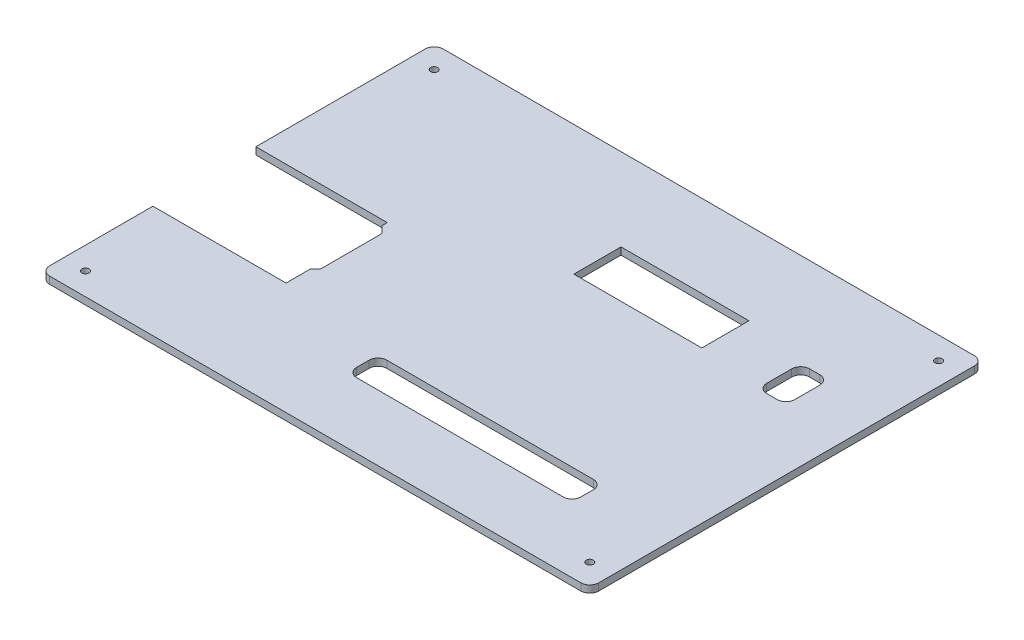
SolidWorks part; units mm, degrees
material "ABS PC"
ref_plane "Front Plane" through (0, 0, 0) normal (0, 0, 1) x (1, 0, 0)
ref_plane "Top Plane" through (0, 0, 0) normal (0, 1, 0) x (1, 0, 0)
ref_plane "Right Plane" through (0, 0, 0) normal (1, 0, 0) x (0, 0, -1)
sketch "Sketch1" plane through (0, 0, 0) normal (0, 1, 0) x (1, 0, 0)
  line L1 (-148.5, -110) -> (148.5, -110)
  line L2 (-153.5, -105) -> (-153.5, 105)
  line L3 (-148.5, 110) -> (148.5, 110)
  line L4 (153.5, -105) -> (153.5, 105)
  line L5 (-153.5, -110) -> (153.5, 110) construction
  line L6 (-153.5, 110) -> (153.5, -110) construction
  arc A0 (148.5, 110) -> (153.5, 105) centre (148.5, 105) cw
  arc A1 (148.5, -110) -> (153.5, -105) centre (148.5, -105) ccw
  arc A2 (-148.5, -110) -> (-153.5, -105) centre (-148.5, -105) cw
  arc A3 (-153.5, 105) -> (-148.5, 110) centre (-148.5, 105) cw
  point P0 (0, 0)
  dimension "D3" = 5
  dimension "D1" = 307
  dimension "D2" = 220
extrude "Boss-Extrude1" add sketch "Sketch1" along normal blind 4
sketch "Sketch3" plane through (0, 4, 0) normal (0, 1, 0) x (1, 0, 0)
  line L0 (-101.7102, 6.397) -> (-102.7298, 6.397)
  line L1 (-102.7298, 6.397) -> (-103.109, 6.0178)
  line L2 (-103.109, 6.0178) -> (-103.109, 3.9822)
  line L3 (-103.109, 3.9822) -> (-102.7298, 3.603)
  line L4 (-102.7298, 3.603) -> (-101.7102, 3.603)
  line L5 (-101.7102, 3.603) -> (-101.331, 3.9822)
  line L6 (-101.331, 3.9822) -> (-101.331, 6.0178)
  line L7 (-101.331, 6.0178) -> (-101.7102, 6.397)
  line L8 (-104.2502, 6.397) -> (-105.2698, 6.397)
  line L9 (-105.2698, 6.397) -> (-105.649, 6.0178)
  line L10 (-105.649, 6.0178) -> (-105.649, 3.9822)
  line L11 (-105.649, 3.9822) -> (-105.2698, 3.603)
  line L12 (-105.2698, 3.603) -> (-104.2502, 3.603)
  line L13 (-104.2502, 3.603) -> (-103.871, 3.9822)
  line L14 (-103.871, 3.9822) -> (-103.871, 6.0178)
  line L15 (-103.871, 6.0178) -> (-104.2502, 6.397)
  line L16 (-106.7902, 6.397) -> (-107.8098, 6.397)
  line L17 (-107.8098, 6.397) -> (-108.189, 6.0178)
  line L18 (-108.189, 6.0178) -> (-108.189, 3.9822)
  line L19 (-108.189, 3.9822) -> (-107.8098, 3.603)
  line L20 (-107.8098, 3.603) -> (-106.7902, 3.603)
  line L21 (-106.7902, 3.603) -> (-106.411, 3.9822)
  line L22 (-106.411, 3.9822) -> (-106.411, 6.0178)
  line L23 (-106.411, 6.0178) -> (-106.7902, 6.397)
  line L24 (-109.3302, 6.397) -> (-110.3498, 6.397)
  line L25 (-110.3498, 6.397) -> (-110.729, 6.0178)
  line L26 (-110.729, 6.0178) -> (-110.729, 3.9822)
  line L27 (-110.729, 3.9822) -> (-110.3498, 3.603)
  line L28 (-110.3498, 3.603) -> (-109.3302, 3.603)
  line L29 (-109.3302, 3.603) -> (-108.951, 3.9822)
  line L30 (-108.951, 3.9822) -> (-108.951, 6.0178)
  line L31 (-108.951, 6.0178) -> (-109.3302, 6.397)
  line L32 (-111.8702, 6.397) -> (-112.8898, 6.397)
  line L33 (-112.8898, 6.397) -> (-113.269, 6.0178)
  line L34 (-113.269, 6.0178) -> (-113.269, 3.9822)
  line L35 (-113.269, 3.9822) -> (-112.8898, 3.603)
  line L36 (-112.8898, 3.603) -> (-111.8702, 3.603)
  line L37 (-111.8702, 3.603) -> (-111.491, 3.9822)
  line L38 (-111.491, 3.9822) -> (-111.491, 6.0178)
  line L39 (-111.491, 6.0178) -> (-111.8702, 6.397)
  line L40 (-114.4102, 6.397) -> (-115.4298, 6.397)
  line L41 (-115.4298, 6.397) -> (-115.809, 6.0178)
  line L42 (-115.809, 6.0178) -> (-115.809, 3.9822)
  line L43 (-115.809, 3.9822) -> (-115.4298, 3.603)
  line L44 (-115.4298, 3.603) -> (-114.4102, 3.603)
  line L45 (-114.4102, 3.603) -> (-114.031, 3.9822)
  line L46 (-114.031, 3.9822) -> (-114.031, 6.0178)
  line L47 (-114.031, 6.0178) -> (-114.4102, 6.397)
  line L48 (-116.9502, 6.397) -> (-117.9698, 6.397)
  line L49 (-117.9698, 6.397) -> (-118.349, 6.0178)
  line L50 (-118.349, 6.0178) -> (-118.349, 3.9822)
  line L51 (-118.349, 3.9822) -> (-117.9698, 3.603)
  line L52 (-117.9698, 3.603) -> (-116.9502, 3.603)
  line L53 (-116.9502, 3.603) -> (-116.571, 3.9822)
  line L54 (-116.571, 3.9822) -> (-116.571, 6.0178)
  line L55 (-116.571, 6.0178) -> (-116.9502, 6.397)
  line L56 (-119.4902, 6.397) -> (-120.5098, 6.397)
  line L57 (-120.5098, 6.397) -> (-120.889, 6.0178)
  line L58 (-120.889, 6.0178) -> (-120.889, 3.9822)
  line L59 (-120.889, 3.9822) -> (-120.5098, 3.603)
  line L60 (-120.5098, 3.603) -> (-119.4902, 3.603)
  line L61 (-119.4902, 3.603) -> (-119.111, 3.9822)
  line L62 (-119.111, 3.9822) -> (-119.111, 6.0178)
  line L63 (-119.111, 6.0178) -> (-119.4902, 6.397)
  line L64 (-97.6498, 6.397) -> (-96.6302, 6.397)
  line L65 (-96.6302, 6.397) -> (-96.251, 6.0178)
  line L66 (-96.251, 6.0178) -> (-96.251, 3.9822)
  line L67 (-96.251, 3.9822) -> (-96.6302, 3.603)
  line L68 (-96.6302, 3.603) -> (-97.6498, 3.603)
  line L69 (-97.6498, 3.603) -> (-98.029, 3.9822)
  line L70 (-98.029, 3.9822) -> (-98.029, 6.0178)
  line L71 (-98.029, 6.0178) -> (-97.6498, 6.397)
  line L72 (-95.1098, 6.397) -> (-94.0902, 6.397)
  line L73 (-94.0902, 6.397) -> (-93.711, 6.0178)
  line L74 (-93.711, 6.0178) -> (-93.711, 3.9822)
  line L75 (-93.711, 3.9822) -> (-94.0902, 3.603)
  line L76 (-94.0902, 3.603) -> (-95.1098, 3.603)
  line L77 (-95.1098, 3.603) -> (-95.489, 3.9822)
  line L78 (-95.489, 3.9822) -> (-95.489, 6.0178)
  line L79 (-95.489, 6.0178) -> (-95.1098, 6.397)
  line L80 (-92.5698, 6.397) -> (-91.5502, 6.397)
  line L81 (-91.5502, 6.397) -> (-91.171, 6.0178)
  line L82 (-91.171, 6.0178) -> (-91.171, 3.9822)
  line L83 (-91.171, 3.9822) -> (-91.5502, 3.603)
  line L84 (-91.5502, 3.603) -> (-92.5698, 3.603)
  line L85 (-92.5698, 3.603) -> (-92.949, 3.9822)
  line L86 (-92.949, 3.9822) -> (-92.949, 6.0178)
  line L87 (-92.949, 6.0178) -> (-92.5698, 6.397)
  line L88 (-90.0298, 6.397) -> (-89.0102, 6.397)
  line L89 (-89.0102, 6.397) -> (-88.631, 6.0178)
  line L90 (-88.631, 6.0178) -> (-88.631, 3.9822)
  line L91 (-88.631, 3.9822) -> (-89.0102, 3.603)
  line L92 (-89.0102, 3.603) -> (-90.0298, 3.603)
  line L93 (-90.0298, 3.603) -> (-90.409, 3.9822)
  line L94 (-90.409, 3.9822) -> (-90.409, 6.0178)
  line L95 (-90.409, 6.0178) -> (-90.0298, 6.397)
  line L96 (-87.4898, 6.397) -> (-86.4702, 6.397)
  line L97 (-86.4702, 6.397) -> (-86.091, 6.0178)
  line L98 (-86.091, 6.0178) -> (-86.091, 3.9822)
  line L99 (-86.091, 3.9822) -> (-86.4702, 3.603)
  line L100 (-86.4702, 3.603) -> (-87.4898, 3.603)
  line L101 (-87.4898, 3.603) -> (-87.869, 3.9822)
  line L102 (-87.869, 3.9822) -> (-87.869, 6.0178)
  line L103 (-87.869, 6.0178) -> (-87.4898, 6.397)
  line L104 (-84.9498, 6.397) -> (-83.9302, 6.397)
  line L105 (-83.9302, 6.397) -> (-83.551, 6.0178)
  line L106 (-83.551, 6.0178) -> (-83.551, 3.9822)
  line L107 (-83.551, 3.9822) -> (-83.9302, 3.603)
  line L108 (-83.9302, 3.603) -> (-84.9498, 3.603)
  line L109 (-84.9498, 3.603) -> (-85.329, 3.9822)
  line L110 (-85.329, 3.9822) -> (-85.329, 6.0178)
  line L111 (-85.329, 6.0178) -> (-84.9498, 6.397)
  line L112 (-83.9302, -41.863) -> (-84.9498, -41.863)
  line L113 (-84.9498, -41.863) -> (-85.329, -42.2422)
  line L114 (-85.329, -42.2422) -> (-85.329, -44.2778)
  line L115 (-85.329, -44.2778) -> (-84.9498, -44.657)
  line L116 (-84.9498, -44.657) -> (-83.9302, -44.657)
  line L117 (-83.9302, -44.657) -> (-83.551, -44.2778)
  line L118 (-83.551, -44.2778) -> (-83.551, -42.2422)
  line L119 (-83.551, -42.2422) -> (-83.9302, -41.863)
  line L120 (-86.4702, -41.863) -> (-87.4898, -41.863)
  line L121 (-87.4898, -41.863) -> (-87.869, -42.2422)
  line L122 (-87.869, -42.2422) -> (-87.869, -44.2778)
  line L123 (-87.869, -44.2778) -> (-87.4898, -44.657)
  line L124 (-87.4898, -44.657) -> (-86.4702, -44.657)
  line L125 (-86.4702, -44.657) -> (-86.091, -44.2778)
  line L126 (-86.091, -44.2778) -> (-86.091, -42.2422)
  line L127 (-86.091, -42.2422) -> (-86.4702, -41.863)
  line L128 (-89.0102, -41.863) -> (-90.0298, -41.863)
  line L129 (-90.0298, -41.863) -> (-90.409, -42.2422)
  line L130 (-90.409, -42.2422) -> (-90.409, -44.2778)
  line L131 (-90.409, -44.2778) -> (-90.0298, -44.657)
  line L132 (-90.0298, -44.657) -> (-89.0102, -44.657)
  line L133 (-89.0102, -44.657) -> (-88.631, -44.2778)
  line L134 (-88.631, -44.2778) -> (-88.631, -42.2422)
  line L135 (-88.631, -42.2422) -> (-89.0102, -41.863)
  line L136 (-91.5502, -41.863) -> (-92.5698, -41.863)
  line L137 (-92.5698, -41.863) -> (-92.949, -42.2422)
  line L138 (-92.949, -42.2422) -> (-92.949, -44.2778)
  line L139 (-92.949, -44.2778) -> (-92.5698, -44.657)
  line L140 (-92.5698, -44.657) -> (-91.5502, -44.657)
  line L141 (-91.5502, -44.657) -> (-91.171, -44.2778)
  line L142 (-91.171, -44.2778) -> (-91.171, -42.2422)
  line L143 (-91.171, -42.2422) -> (-91.5502, -41.863)
  line L144 (-94.0902, -41.863) -> (-95.1098, -41.863)
  line L145 (-95.1098, -41.863) -> (-95.489, -42.2422)
  line L146 (-95.489, -42.2422) -> (-95.489, -44.2778)
  line L147 (-95.489, -44.2778) -> (-95.1098, -44.657)
  line L148 (-95.1098, -44.657) -> (-94.0902, -44.657)
  line L149 (-94.0902, -44.657) -> (-93.711, -44.2778)
  line L150 (-93.711, -44.2778) -> (-93.711, -42.2422)
  line L151 (-93.711, -42.2422) -> (-94.0902, -41.863)
  line L152 (-96.6302, -41.863) -> (-97.6498, -41.863)
  line L153 (-97.6498, -41.863) -> (-98.029, -42.2422)
  line L154 (-98.029, -42.2422) -> (-98.029, -44.2778)
  line L155 (-98.029, -44.2778) -> (-97.6498, -44.657)
  line L156 (-97.6498, -44.657) -> (-96.6302, -44.657)
  line L157 (-96.6302, -44.657) -> (-96.251, -44.2778)
  line L158 (-96.251, -44.2778) -> (-96.251, -42.2422)
  line L159 (-96.251, -42.2422) -> (-96.6302, -41.863)
  line L160 (-99.1702, -41.863) -> (-100.1898, -41.863)
  line L161 (-100.1898, -41.863) -> (-100.569, -42.2422)
  line L162 (-100.569, -42.2422) -> (-100.569, -44.2778)
  line L163 (-100.569, -44.2778) -> (-100.1898, -44.657)
  line L164 (-100.1898, -44.657) -> (-99.1702, -44.657)
  line L165 (-99.1702, -44.657) -> (-98.791, -44.2778)
  line L166 (-98.791, -44.2778) -> (-98.791, -42.2422)
  line L167 (-98.791, -42.2422) -> (-99.1702, -41.863)
  line L168 (-101.7102, -41.863) -> (-102.7298, -41.863)
  line L169 (-102.7298, -41.863) -> (-103.109, -42.2422)
  line L170 (-103.109, -42.2422) -> (-103.109, -44.2778)
  line L171 (-103.109, -44.2778) -> (-102.7298, -44.657)
  line L172 (-102.7298, -44.657) -> (-101.7102, -44.657)
  line L173 (-101.7102, -44.657) -> (-101.331, -44.2778)
  line L174 (-101.331, -44.2778) -> (-101.331, -42.2422)
  line L175 (-101.331, -42.2422) -> (-101.7102, -41.863)
  line L176 (-105.5202, -41.863) -> (-106.5398, -41.863)
  line L177 (-106.5398, -41.863) -> (-106.919, -42.2422)
  line L178 (-106.919, -42.2422) -> (-106.919, -44.2778)
  line L179 (-106.919, -44.2778) -> (-106.5398, -44.657)
  line L180 (-106.5398, -44.657) -> (-105.5202, -44.657)
  line L181 (-105.5202, -44.657) -> (-105.141, -44.2778)
  line L182 (-105.141, -44.2778) -> (-105.141, -42.2422)
  line L183 (-105.141, -42.2422) -> (-105.5202, -41.863)
  line L184 (-108.0602, -41.863) -> (-109.0798, -41.863)
  line L185 (-109.0798, -41.863) -> (-109.459, -42.2422)
  line L186 (-109.459, -42.2422) -> (-109.459, -44.2778)
  line L187 (-109.459, -44.2778) -> (-109.0798, -44.657)
  line L188 (-109.0798, -44.657) -> (-108.0602, -44.657)
  line L189 (-108.0602, -44.657) -> (-107.681, -44.2778)
  line L190 (-107.681, -44.2778) -> (-107.681, -42.2422)
  line L191 (-107.681, -42.2422) -> (-108.0602, -41.863)
  line L192 (-110.6002, -41.863) -> (-111.6198, -41.863)
  line L193 (-111.6198, -41.863) -> (-111.999, -42.2422)
  line L194 (-111.999, -42.2422) -> (-111.999, -44.2778)
  line L195 (-111.999, -44.2778) -> (-111.6198, -44.657)
  line L196 (-111.6198, -44.657) -> (-110.6002, -44.657)
  line L197 (-110.6002, -44.657) -> (-110.221, -44.2778)
  line L198 (-110.221, -44.2778) -> (-110.221, -42.2422)
  line L199 (-110.221, -42.2422) -> (-110.6002, -41.863)
  line L200 (-113.1402, -41.863) -> (-114.1598, -41.863)
  line L201 (-114.1598, -41.863) -> (-114.539, -42.2422)
  line L202 (-114.539, -42.2422) -> (-114.539, -44.2778)
  line L203 (-114.539, -44.2778) -> (-114.1598, -44.657)
  line L204 (-114.1598, -44.657) -> (-113.1402, -44.657)
  line L205 (-113.1402, -44.657) -> (-112.761, -44.2778)
  line L206 (-112.761, -44.2778) -> (-112.761, -42.2422)
  line L207 (-112.761, -42.2422) -> (-113.1402, -41.863)
  line L208 (-115.6802, -41.863) -> (-116.6998, -41.863)
  line L209 (-116.6998, -41.863) -> (-117.079, -42.2422)
  line L210 (-117.079, -42.2422) -> (-117.079, -44.2778)
  line L211 (-117.079, -44.2778) -> (-116.6998, -44.657)
  line L212 (-116.6998, -44.657) -> (-115.6802, -44.657)
  line L213 (-115.6802, -44.657) -> (-115.301, -44.2778)
  line L214 (-115.301, -44.2778) -> (-115.301, -42.2422)
  line L215 (-115.301, -42.2422) -> (-115.6802, -41.863)
  line L216 (-118.2202, -41.863) -> (-119.2398, -41.863)
  line L217 (-119.2398, -41.863) -> (-119.619, -42.2422)
  line L218 (-119.619, -42.2422) -> (-119.619, -44.2778)
  line L219 (-119.619, -44.2778) -> (-119.2398, -44.657)
  line L220 (-119.2398, -44.657) -> (-118.2202, -44.657)
  line L221 (-118.2202, -44.657) -> (-117.841, -44.2778)
  line L222 (-117.841, -44.2778) -> (-117.841, -42.2422)
  line L223 (-117.841, -42.2422) -> (-118.2202, -41.863)
  line L224 (-120.7602, -41.863) -> (-121.7798, -41.863)
  line L225 (-121.7798, -41.863) -> (-122.159, -42.2422)
  line L226 (-122.159, -42.2422) -> (-122.159, -44.2778)
  line L227 (-122.159, -44.2778) -> (-121.7798, -44.657)
  line L228 (-121.7798, -44.657) -> (-120.7602, -44.657)
  line L229 (-120.7602, -44.657) -> (-120.381, -44.2778)
  line L230 (-120.381, -44.2778) -> (-120.381, -42.2422)
  line L231 (-120.381, -42.2422) -> (-120.7602, -41.863)
  line L232 (-123.3002, -41.863) -> (-124.3198, -41.863)
  line L233 (-124.3198, -41.863) -> (-124.699, -42.2422)
  line L234 (-124.699, -42.2422) -> (-124.699, -44.2778)
  line L235 (-124.699, -44.2778) -> (-124.3198, -44.657)
  line L236 (-124.3198, -44.657) -> (-123.3002, -44.657)
  line L237 (-123.3002, -44.657) -> (-122.921, -44.2778)
  line L238 (-122.921, -44.2778) -> (-122.921, -42.2422)
  line L239 (-122.921, -42.2422) -> (-123.3002, -41.863)
  line L240 (-125.8402, -41.863) -> (-126.8598, -41.863)
  line L241 (-126.8598, -41.863) -> (-127.239, -42.2422)
  line L242 (-127.239, -42.2422) -> (-127.239, -44.2778)
  line L243 (-127.239, -44.2778) -> (-126.8598, -44.657)
  line L244 (-126.8598, -44.657) -> (-125.8402, -44.657)
  line L245 (-125.8402, -44.657) -> (-125.461, -44.2778)
  line L246 (-125.461, -44.2778) -> (-125.461, -42.2422)
  line L247 (-125.461, -42.2422) -> (-125.8402, -41.863)
  line L248 (-128.3802, -41.863) -> (-129.3998, -41.863)
  line L249 (-129.3998, -41.863) -> (-129.779, -42.2422)
  line L250 (-129.779, -42.2422) -> (-129.779, -44.2778)
  line L251 (-129.779, -44.2778) -> (-129.3998, -44.657)
  line L252 (-129.3998, -44.657) -> (-128.3802, -44.657)
  line L253 (-128.3802, -44.657) -> (-128.001, -44.2778)
  line L254 (-128.001, -44.2778) -> (-128.001, -42.2422)
  line L255 (-128.001, -42.2422) -> (-128.3802, -41.863)
  line L256 (-4.887, -62.244) -> (-4.887, -64.276)
  line L257 (-4.887, -64.276) -> (-4.8895, -64.302)
  line L258 (-4.8895, -64.302) -> (-4.8968, -64.326)
  line L259 (-4.8968, -64.326) -> (-4.9083, -64.3476)
  line L260 (-4.9083, -64.3476) -> (-4.9237, -64.3663)
  line L261 (-4.9237, -64.3663) -> (-4.9424, -64.3817)
  line L262 (-4.9424, -64.3817) -> (-4.964, -64.3932)
  line L263 (-4.964, -64.3932) -> (-4.988, -64.4005)
  line L264 (-4.988, -64.4005) -> (-5.014, -64.403)
  line L265 (-5.014, -64.403) -> (-7.046, -64.403)
  line L266 (-7.046, -64.403) -> (-7.072, -64.4005)
  line L267 (-7.072, -64.4005) -> (-7.096, -64.3932)
  line L268 (-7.096, -64.3932) -> (-7.1176, -64.3817)
  line L269 (-7.1176, -64.3817) -> (-7.1363, -64.3663)
  line L270 (-7.1363, -64.3663) -> (-7.1516, -64.3476)
  line L271 (-7.1516, -64.3476) -> (-7.1632, -64.326)
  line L272 (-7.1632, -64.326) -> (-7.1705, -64.302)
  line L273 (-7.1705, -64.302) -> (-7.173, -64.276)
  line L274 (-7.173, -64.276) -> (-7.173, -62.244)
  line L275 (-7.173, -62.244) -> (-7.1705, -62.218)
  line L276 (-7.1705, -62.218) -> (-7.1632, -62.194)
  line L277 (-7.1632, -62.194) -> (-7.1516, -62.1724)
  line L278 (-7.1516, -62.1724) -> (-7.1363, -62.1537)
  line L279 (-7.1363, -62.1537) -> (-7.1176, -62.1384)
  line L280 (-7.1176, -62.1384) -> (-7.096, -62.1268)
  line L281 (-7.096, -62.1268) -> (-7.072, -62.1195)
  line L282 (-7.072, -62.1195) -> (-7.046, -62.117)
  line L283 (-7.046, -62.117) -> (-5.014, -62.117)
  line L284 (-5.014, -62.117) -> (-4.988, -62.1195)
  line L285 (-4.988, -62.1195) -> (-4.964, -62.1268)
  line L286 (-4.964, -62.1268) -> (-4.9424, -62.1384)
  line L287 (-4.9424, -62.1384) -> (-4.9237, -62.1537)
  line L288 (-4.9237, -62.1537) -> (-4.9083, -62.1724)
  line L289 (-4.9083, -62.1724) -> (-4.8968, -62.194)
  line L290 (-4.8968, -62.194) -> (-4.8895, -62.218)
  line L291 (-4.8895, -62.218) -> (-4.887, -62.244)
  line L292 (-4.887, -64.784) -> (-4.887, -66.816)
  line L293 (-4.887, -66.816) -> (-4.8895, -66.842)
  line L294 (-4.8895, -66.842) -> (-4.8968, -66.866)
  line L295 (-4.8968, -66.866) -> (-4.9083, -66.8876)
  line L296 (-4.9083, -66.8876) -> (-4.9237, -66.9063)
  line L297 (-4.9237, -66.9063) -> (-4.9424, -66.9217)
  line L298 (-4.9424, -66.9217) -> (-4.964, -66.9332)
  line L299 (-4.964, -66.9332) -> (-4.988, -66.9405)
  line L300 (-4.988, -66.9405) -> (-5.014, -66.943)
  line L301 (-5.014, -66.943) -> (-7.046, -66.943)
  line L302 (-7.046, -66.943) -> (-7.072, -66.9405)
  line L303 (-7.072, -66.9405) -> (-7.096, -66.9332)
  line L304 (-7.096, -66.9332) -> (-7.1176, -66.9217)
  line L305 (-7.1176, -66.9217) -> (-7.1363, -66.9063)
  line L306 (-7.1363, -66.9063) -> (-7.1516, -66.8876)
  line L307 (-7.1516, -66.8876) -> (-7.1632, -66.866)
  line L308 (-7.1632, -66.866) -> (-7.1705, -66.842)
  line L309 (-7.1705, -66.842) -> (-7.173, -66.816)
  line L310 (-7.173, -66.816) -> (-7.173, -64.784)
  line L311 (-7.173, -64.784) -> (-7.1705, -64.758)
  line L312 (-7.1705, -64.758) -> (-7.1632, -64.734)
  line L313 (-7.1632, -64.734) -> (-7.1516, -64.7124)
  line L314 (-7.1516, -64.7124) -> (-7.1363, -64.6937)
  line L315 (-7.1363, -64.6937) -> (-7.1176, -64.6784)
  line L316 (-7.1176, -64.6784) -> (-7.096, -64.6668)
  line L317 (-7.096, -64.6668) -> (-7.072, -64.6595)
  line L318 (-7.072, -64.6595) -> (-7.046, -64.657)
  line L319 (-7.046, -64.657) -> (-5.014, -64.657)
  line L320 (-5.014, -64.657) -> (-4.988, -64.6595)
  line L321 (-4.988, -64.6595) -> (-4.964, -64.6668)
  line L322 (-4.964, -64.6668) -> (-4.9424, -64.6784)
  line L323 (-4.9424, -64.6784) -> (-4.9237, -64.6937)
  line L324 (-4.9237, -64.6937) -> (-4.9083, -64.7124)
  line L325 (-4.9083, -64.7124) -> (-4.8968, -64.734)
  line L326 (-4.8968, -64.734) -> (-4.8895, -64.758)
  line L327 (-4.8895, -64.758) -> (-4.887, -64.784)
  line L328 (15.113, -62.244) -> (15.113, -64.276)
  line L329 (15.113, -64.276) -> (15.1105, -64.302)
  line L330 (15.1105, -64.302) -> (15.1032, -64.326)
  line L331 (15.1032, -64.326) -> (15.0916, -64.3476)
  line L332 (15.0916, -64.3476) -> (15.0763, -64.3663)
  line L333 (15.0763, -64.3663) -> (15.0576, -64.3817)
  line L334 (15.0576, -64.3817) -> (15.036, -64.3932)
  line L335 (15.036, -64.3932) -> (15.012, -64.4005)
  line L336 (15.012, -64.4005) -> (14.986, -64.403)
  line L337 (14.986, -64.403) -> (12.954, -64.403)
  line L338 (12.954, -64.403) -> (12.928, -64.4005)
  line L339 (12.928, -64.4005) -> (12.904, -64.3932)
  line L340 (12.904, -64.3932) -> (12.8824, -64.3817)
  line L341 (12.8824, -64.3817) -> (12.8637, -64.3663)
  line L342 (12.8637, -64.3663) -> (12.8484, -64.3476)
  line L343 (12.8484, -64.3476) -> (12.8368, -64.326)
  line L344 (12.8368, -64.326) -> (12.8295, -64.302)
  line L345 (12.8295, -64.302) -> (12.827, -64.276)
  line L346 (12.827, -64.276) -> (12.827, -62.244)
  line L347 (12.827, -62.244) -> (12.8295, -62.218)
  line L348 (12.8295, -62.218) -> (12.8368, -62.194)
  line L349 (12.8368, -62.194) -> (12.8484, -62.1724)
  line L350 (12.8484, -62.1724) -> (12.8637, -62.1537)
  line L351 (12.8637, -62.1537) -> (12.8824, -62.1384)
  line L352 (12.8824, -62.1384) -> (12.904, -62.1268)
  line L353 (12.904, -62.1268) -> (12.928, -62.1195)
  line L354 (12.928, -62.1195) -> (12.954, -62.117)
  line L355 (12.954, -62.117) -> (14.986, -62.117)
  line L356 (14.986, -62.117) -> (15.012, -62.1195)
  line L357 (15.012, -62.1195) -> (15.036, -62.1268)
  line L358 (15.036, -62.1268) -> (15.0576, -62.1384)
  line L359 (15.0576, -62.1384) -> (15.0763, -62.1537)
  line L360 (15.0763, -62.1537) -> (15.0916, -62.1724)
  line L361 (15.0916, -62.1724) -> (15.1032, -62.194)
  line L362 (15.1032, -62.194) -> (15.1105, -62.218)
  line L363 (15.1105, -62.218) -> (15.113, -62.244)
  line L364 (15.113, -64.784) -> (15.113, -66.816)
  line L365 (15.113, -66.816) -> (15.1105, -66.842)
  line L366 (15.1105, -66.842) -> (15.1032, -66.866)
  line L367 (15.1032, -66.866) -> (15.0916, -66.8876)
  line L368 (15.0916, -66.8876) -> (15.0763, -66.9063)
  line L369 (15.0763, -66.9063) -> (15.0576, -66.9217)
  line L370 (15.0576, -66.9217) -> (15.036, -66.9332)
  line L371 (15.036, -66.9332) -> (15.012, -66.9405)
  line L372 (15.012, -66.9405) -> (14.986, -66.943)
  line L373 (14.986, -66.943) -> (12.954, -66.943)
  line L374 (12.954, -66.943) -> (12.928, -66.9405)
  line L375 (12.928, -66.9405) -> (12.904, -66.9332)
  line L376 (12.904, -66.9332) -> (12.8824, -66.9217)
  line L377 (12.8824, -66.9217) -> (12.8637, -66.9063)
  line L378 (12.8637, -66.9063) -> (12.8484, -66.8876)
  line L379 (12.8484, -66.8876) -> (12.8368, -66.866)
  line L380 (12.8368, -66.866) -> (12.8295, -66.842)
  line L381 (12.8295, -66.842) -> (12.827, -66.816)
  line L382 (12.827, -66.816) -> (12.827, -64.784)
  line L383 (12.827, -64.784) -> (12.8295, -64.758)
  line L384 (12.8295, -64.758) -> (12.8368, -64.734)
  line L385 (12.8368, -64.734) -> (12.8484, -64.7124)
  line L386 (12.8484, -64.7124) -> (12.8637, -64.6937)
  line L387 (12.8637, -64.6937) -> (12.8824, -64.6784)
  line L388 (12.8824, -64.6784) -> (12.904, -64.6668)
  line L389 (12.904, -64.6668) -> (12.928, -64.6595)
  line L390 (12.928, -64.6595) -> (12.954, -64.657)
  line L391 (12.954, -64.657) -> (14.986, -64.657)
  line L392 (14.986, -64.657) -> (15.012, -64.6595)
  line L393 (15.012, -64.6595) -> (15.036, -64.6668)
  line L394 (15.036, -64.6668) -> (15.0576, -64.6784)
  line L395 (15.0576, -64.6784) -> (15.0763, -64.6937)
  line L396 (15.0763, -64.6937) -> (15.0916, -64.7124)
  line L397 (15.0916, -64.7124) -> (15.1032, -64.734)
  line L398 (15.1032, -64.734) -> (15.1105, -64.758)
  line L399 (15.1105, -64.758) -> (15.113, -64.784)
  line L400 (35.113, -62.244) -> (35.113, -64.276)
  line L401 (35.113, -64.276) -> (35.1105, -64.302)
  line L402 (35.1105, -64.302) -> (35.1032, -64.326)
  line L403 (35.1032, -64.326) -> (35.0916, -64.3476)
  line L404 (35.0916, -64.3476) -> (35.0763, -64.3663)
  line L405 (35.0763, -64.3663) -> (35.0576, -64.3817)
  line L406 (35.0576, -64.3817) -> (35.036, -64.3932)
  line L407 (35.036, -64.3932) -> (35.012, -64.4005)
  line L408 (35.012, -64.4005) -> (34.986, -64.403)
  line L409 (34.986, -64.403) -> (32.954, -64.403)
  line L410 (32.954, -64.403) -> (32.928, -64.4005)
  line L411 (32.928, -64.4005) -> (32.904, -64.3932)
  line L412 (32.904, -64.3932) -> (32.8824, -64.3817)
  line L413 (32.8824, -64.3817) -> (32.8637, -64.3663)
  line L414 (32.8637, -64.3663) -> (32.8483, -64.3476)
  line L415 (32.8483, -64.3476) -> (32.8368, -64.326)
  line L416 (32.8368, -64.326) -> (32.8295, -64.302)
  line L417 (32.8295, -64.302) -> (32.827, -64.276)
  line L418 (32.827, -64.276) -> (32.827, -62.244)
  line L419 (32.827, -62.244) -> (32.8295, -62.218)
  line L420 (32.8295, -62.218) -> (32.8368, -62.194)
  line L421 (32.8368, -62.194) -> (32.8483, -62.1724)
  line L422 (32.8483, -62.1724) -> (32.8637, -62.1537)
  line L423 (32.8637, -62.1537) -> (32.8824, -62.1384)
  line L424 (32.8824, -62.1384) -> (32.904, -62.1268)
  line L425 (32.904, -62.1268) -> (32.928, -62.1195)
  line L426 (32.928, -62.1195) -> (32.954, -62.117)
  line L427 (32.954, -62.117) -> (34.986, -62.117)
  line L428 (34.986, -62.117) -> (35.012, -62.1195)
  line L429 (35.012, -62.1195) -> (35.036, -62.1268)
  line L430 (35.036, -62.1268) -> (35.0576, -62.1384)
  line L431 (35.0576, -62.1384) -> (35.0763, -62.1537)
  line L432 (35.0763, -62.1537) -> (35.0916, -62.1724)
  line L433 (35.0916, -62.1724) -> (35.1032, -62.194)
  line L434 (35.1032, -62.194) -> (35.1105, -62.218)
  line L435 (35.1105, -62.218) -> (35.113, -62.244)
  line L436 (35.113, -64.784) -> (35.113, -66.816)
  line L437 (35.113, -66.816) -> (35.1105, -66.842)
  line L438 (35.1105, -66.842) -> (35.1032, -66.866)
  line L439 (35.1032, -66.866) -> (35.0916, -66.8876)
  line L440 (35.0916, -66.8876) -> (35.0763, -66.9063)
  line L441 (35.0763, -66.9063) -> (35.0576, -66.9217)
  line L442 (35.0576, -66.9217) -> (35.036, -66.9332)
  line L443 (35.036, -66.9332) -> (35.012, -66.9405)
  line L444 (35.012, -66.9405) -> (34.986, -66.943)
  line L445 (34.986, -66.943) -> (32.954, -66.943)
  line L446 (32.954, -66.943) -> (32.928, -66.9405)
  line L447 (32.928, -66.9405) -> (32.904, -66.9332)
  line L448 (32.904, -66.9332) -> (32.8824, -66.9217)
  line L449 (32.8824, -66.9217) -> (32.8637, -66.9063)
  line L450 (32.8637, -66.9063) -> (32.8483, -66.8876)
  line L451 (32.8483, -66.8876) -> (32.8368, -66.866)
  line L452 (32.8368, -66.866) -> (32.8295, -66.842)
  line L453 (32.8295, -66.842) -> (32.827, -66.816)
  line L454 (32.827, -66.816) -> (32.827, -64.784)
  line L455 (32.827, -64.784) -> (32.8295, -64.758)
  line L456 (32.8295, -64.758) -> (32.8368, -64.734)
  line L457 (32.8368, -64.734) -> (32.8483, -64.7124)
  line L458 (32.8483, -64.7124) -> (32.8637, -64.6937)
  line L459 (32.8637, -64.6937) -> (32.8824, -64.6784)
  line L460 (32.8824, -64.6784) -> (32.904, -64.6668)
  line L461 (32.904, -64.6668) -> (32.928, -64.6595)
  line L462 (32.928, -64.6595) -> (32.954, -64.657)
  line L463 (32.954, -64.657) -> (34.986, -64.657)
  line L464 (34.986, -64.657) -> (35.012, -64.6595)
  line L465 (35.012, -64.6595) -> (35.036, -64.6668)
  line L466 (35.036, -64.6668) -> (35.0576, -64.6784)
  line L467 (35.0576, -64.6784) -> (35.0763, -64.6937)
  line L468 (35.0763, -64.6937) -> (35.0916, -64.7124)
  line L469 (35.0916, -64.7124) -> (35.1032, -64.734)
  line L470 (35.1032, -64.734) -> (35.1105, -64.758)
  line L471 (35.1105, -64.758) -> (35.113, -64.784)
  line L472 (55.113, -62.244) -> (55.113, -64.276)
  line L473 (55.113, -64.276) -> (55.1105, -64.302)
  line L474 (55.1105, -64.302) -> (55.1032, -64.326)
  line L475 (55.1032, -64.326) -> (55.0917, -64.3476)
  line L476 (55.0917, -64.3476) -> (55.0763, -64.3663)
  line L477 (55.0763, -64.3663) -> (55.0576, -64.3817)
  line L478 (55.0576, -64.3817) -> (55.036, -64.3932)
  line L479 (55.036, -64.3932) -> (55.012, -64.4005)
  line L480 (55.012, -64.4005) -> (54.986, -64.403)
  line L481 (54.986, -64.403) -> (52.954, -64.403)
  line L482 (52.954, -64.403) -> (52.928, -64.4005)
  line L483 (52.928, -64.4005) -> (52.904, -64.3932)
  line L484 (52.904, -64.3932) -> (52.8824, -64.3817)
  line L485 (52.8824, -64.3817) -> (52.8637, -64.3663)
  line L486 (52.8637, -64.3663) -> (52.8484, -64.3476)
  line L487 (52.8484, -64.3476) -> (52.8368, -64.326)
  line L488 (52.8368, -64.326) -> (52.8295, -64.302)
  line L489 (52.8295, -64.302) -> (52.827, -64.276)
  line L490 (52.827, -64.276) -> (52.827, -62.244)
  line L491 (52.827, -62.244) -> (52.8295, -62.218)
  line L492 (52.8295, -62.218) -> (52.8368, -62.194)
  line L493 (52.8368, -62.194) -> (52.8484, -62.1724)
  line L494 (52.8484, -62.1724) -> (52.8637, -62.1537)
  line L495 (52.8637, -62.1537) -> (52.8824, -62.1384)
  line L496 (52.8824, -62.1384) -> (52.904, -62.1268)
  line L497 (52.904, -62.1268) -> (52.928, -62.1195)
  line L498 (52.928, -62.1195) -> (52.954, -62.117)
  line L499 (52.954, -62.117) -> (54.986, -62.117)
  line L500 (54.986, -62.117) -> (55.012, -62.1195)
  line L501 (55.012, -62.1195) -> (55.036, -62.1268)
  line L502 (55.036, -62.1268) -> (55.0576, -62.1384)
  line L503 (55.0576, -62.1384) -> (55.0763, -62.1537)
  line L504 (55.0763, -62.1537) -> (55.0917, -62.1724)
  line L505 (55.0917, -62.1724) -> (55.1032, -62.194)
  line L506 (55.1032, -62.194) -> (55.1105, -62.218)
  line L507 (55.1105, -62.218) -> (55.113, -62.244)
  line L508 (55.113, -64.784) -> (55.113, -66.816)
  line L509 (55.113, -66.816) -> (55.1105, -66.842)
  line L510 (55.1105, -66.842) -> (55.1032, -66.866)
  line L511 (55.1032, -66.866) -> (55.0917, -66.8876)
  line L512 (55.0917, -66.8876) -> (55.0763, -66.9063)
  line L513 (55.0763, -66.9063) -> (55.0576, -66.9217)
  line L514 (55.0576, -66.9217) -> (55.036, -66.9332)
  line L515 (55.036, -66.9332) -> (55.012, -66.9405)
  line L516 (55.012, -66.9405) -> (54.986, -66.943)
  line L517 (54.986, -66.943) -> (52.954, -66.943)
  line L518 (52.954, -66.943) -> (52.928, -66.9405)
  line L519 (52.928, -66.9405) -> (52.904, -66.9332)
  line L520 (52.904, -66.9332) -> (52.8824, -66.9217)
  line L521 (52.8824, -66.9217) -> (52.8637, -66.9063)
  line L522 (52.8637, -66.9063) -> (52.8484, -66.8876)
  line L523 (52.8484, -66.8876) -> (52.8368, -66.866)
  line L524 (52.8368, -66.866) -> (52.8295, -66.842)
  line L525 (52.8295, -66.842) -> (52.827, -66.816)
  line L526 (52.827, -66.816) -> (52.827, -64.784)
  line L527 (52.827, -64.784) -> (52.8295, -64.758)
  line L528 (52.8295, -64.758) -> (52.8368, -64.734)
  line L529 (52.8368, -64.734) -> (52.8484, -64.7124)
  line L530 (52.8484, -64.7124) -> (52.8637, -64.6937)
  line L531 (52.8637, -64.6937) -> (52.8824, -64.6784)
  line L532 (52.8824, -64.6784) -> (52.904, -64.6668)
  line L533 (52.904, -64.6668) -> (52.928, -64.6595)
  line L534 (52.928, -64.6595) -> (52.954, -64.657)
  line L535 (52.954, -64.657) -> (54.986, -64.657)
  line L536 (54.986, -64.657) -> (55.012, -64.6595)
  line L537 (55.012, -64.6595) -> (55.036, -64.6668)
  line L538 (55.036, -64.6668) -> (55.0576, -64.6784)
  line L539 (55.0576, -64.6784) -> (55.0763, -64.6937)
  line L540 (55.0763, -64.6937) -> (55.0917, -64.7124)
  line L541 (55.0917, -64.7124) -> (55.1032, -64.734)
  line L542 (55.1032, -64.734) -> (55.1105, -64.758)
  line L543 (55.1105, -64.758) -> (55.113, -64.784)
  line L544 (75.113, -62.244) -> (75.113, -64.276)
  line L545 (75.113, -64.276) -> (75.1105, -64.302)
  line L546 (75.1105, -64.302) -> (75.1032, -64.326)
  line L547 (75.1032, -64.326) -> (75.0916, -64.3476)
  line L548 (75.0916, -64.3476) -> (75.0763, -64.3663)
  line L549 (75.0763, -64.3663) -> (75.0576, -64.3817)
  line L550 (75.0576, -64.3817) -> (75.036, -64.3932)
  line L551 (75.036, -64.3932) -> (75.012, -64.4005)
  line L552 (75.012, -64.4005) -> (74.986, -64.403)
  line L553 (74.986, -64.403) -> (72.954, -64.403)
  line L554 (72.954, -64.403) -> (72.928, -64.4005)
  line L555 (72.928, -64.4005) -> (72.904, -64.3932)
  line L556 (72.904, -64.3932) -> (72.8824, -64.3817)
  line L557 (72.8824, -64.3817) -> (72.8637, -64.3663)
  line L558 (72.8637, -64.3663) -> (72.8483, -64.3476)
  line L559 (72.8483, -64.3476) -> (72.8368, -64.326)
  line L560 (72.8368, -64.326) -> (72.8295, -64.302)
  line L561 (72.8295, -64.302) -> (72.827, -64.276)
  line L562 (72.827, -64.276) -> (72.827, -62.244)
  line L563 (72.827, -62.244) -> (72.8295, -62.218)
  line L564 (72.8295, -62.218) -> (72.8368, -62.194)
  line L565 (72.8368, -62.194) -> (72.8483, -62.1724)
  line L566 (72.8483, -62.1724) -> (72.8637, -62.1537)
  line L567 (72.8637, -62.1537) -> (72.8824, -62.1384)
  line L568 (72.8824, -62.1384) -> (72.904, -62.1268)
  line L569 (72.904, -62.1268) -> (72.928, -62.1195)
  line L570 (72.928, -62.1195) -> (72.954, -62.117)
  line L571 (72.954, -62.117) -> (74.986, -62.117)
  line L572 (74.986, -62.117) -> (75.012, -62.1195)
  line L573 (75.012, -62.1195) -> (75.036, -62.1268)
  line L574 (75.036, -62.1268) -> (75.0576, -62.1384)
  line L575 (75.0576, -62.1384) -> (75.0763, -62.1537)
  line L576 (75.0763, -62.1537) -> (75.0916, -62.1724)
  line L577 (75.0916, -62.1724) -> (75.1032, -62.194)
  line L578 (75.1032, -62.194) -> (75.1105, -62.218)
  line L579 (75.1105, -62.218) -> (75.113, -62.244)
  line L580 (75.113, -64.784) -> (75.113, -66.816)
  line L581 (75.113, -66.816) -> (75.1105, -66.842)
  line L582 (75.1105, -66.842) -> (75.1032, -66.866)
  line L583 (75.1032, -66.866) -> (75.0916, -66.8876)
  line L584 (75.0916, -66.8876) -> (75.0763, -66.9063)
  line L585 (75.0763, -66.9063) -> (75.0576, -66.9217)
  line L586 (75.0576, -66.9217) -> (75.036, -66.9332)
  line L587 (75.036, -66.9332) -> (75.012, -66.9405)
  line L588 (75.012, -66.9405) -> (74.986, -66.943)
  line L589 (74.986, -66.943) -> (72.954, -66.943)
  line L590 (72.954, -66.943) -> (72.928, -66.9405)
  line L591 (72.928, -66.9405) -> (72.904, -66.9332)
  line L592 (72.904, -66.9332) -> (72.8824, -66.9217)
  line L593 (72.8824, -66.9217) -> (72.8637, -66.9063)
  line L594 (72.8637, -66.9063) -> (72.8483, -66.8876)
  line L595 (72.8483, -66.8876) -> (72.8368, -66.866)
  line L596 (72.8368, -66.866) -> (72.8295, -66.842)
  line L597 (72.8295, -66.842) -> (72.827, -66.816)
  line L598 (72.827, -66.816) -> (72.827, -64.784)
  line L599 (72.827, -64.784) -> (72.8295, -64.758)
  line L600 (72.8295, -64.758) -> (72.8368, -64.734)
  line L601 (72.8368, -64.734) -> (72.8483, -64.7124)
  line L602 (72.8483, -64.7124) -> (72.8637, -64.6937)
  line L603 (72.8637, -64.6937) -> (72.8824, -64.6784)
  line L604 (72.8824, -64.6784) -> (72.904, -64.6668)
  line L605 (72.904, -64.6668) -> (72.928, -64.6595)
  line L606 (72.928, -64.6595) -> (72.954, -64.657)
  line L607 (72.954, -64.657) -> (74.986, -64.657)
  line L608 (74.986, -64.657) -> (75.012, -64.6595)
  line L609 (75.012, -64.6595) -> (75.036, -64.6668)
  line L610 (75.036, -64.6668) -> (75.0576, -64.6784)
  line L611 (75.0576, -64.6784) -> (75.0763, -64.6937)
  line L612 (75.0763, -64.6937) -> (75.0916, -64.7124)
  line L613 (75.0916, -64.7124) -> (75.1032, -64.734)
  line L614 (75.1032, -64.734) -> (75.1105, -64.758)
  line L615 (75.1105, -64.758) -> (75.113, -64.784)
  line L616 (95.113, -62.244) -> (95.113, -64.276)
  line L617 (95.113, -64.276) -> (95.1105, -64.302)
  line L618 (95.1105, -64.302) -> (95.1032, -64.326)
  line L619 (95.1032, -64.326) -> (95.0917, -64.3476)
  line L620 (95.0917, -64.3476) -> (95.0763, -64.3663)
  line L621 (95.0763, -64.3663) -> (95.0576, -64.3817)
  line L622 (95.0576, -64.3817) -> (95.036, -64.3932)
  line L623 (95.036, -64.3932) -> (95.012, -64.4005)
  line L624 (95.012, -64.4005) -> (94.986, -64.403)
  line L625 (94.986, -64.403) -> (92.954, -64.403)
  line L626 (92.954, -64.403) -> (92.928, -64.4005)
  line L627 (92.928, -64.4005) -> (92.904, -64.3932)
  line L628 (92.904, -64.3932) -> (92.8824, -64.3817)
  line L629 (92.8824, -64.3817) -> (92.8637, -64.3663)
  line L630 (92.8637, -64.3663) -> (92.8484, -64.3476)
  line L631 (92.8484, -64.3476) -> (92.8368, -64.326)
  line L632 (92.8368, -64.326) -> (92.8295, -64.302)
  line L633 (92.8295, -64.302) -> (92.827, -64.276)
  line L634 (92.827, -64.276) -> (92.827, -62.244)
  line L635 (92.827, -62.244) -> (92.8295, -62.218)
  line L636 (92.8295, -62.218) -> (92.8368, -62.194)
  line L637 (92.8368, -62.194) -> (92.8484, -62.1724)
  line L638 (92.8484, -62.1724) -> (92.8637, -62.1537)
  line L639 (92.8637, -62.1537) -> (92.8824, -62.1384)
  line L640 (92.8824, -62.1384) -> (92.904, -62.1268)
  line L641 (92.904, -62.1268) -> (92.928, -62.1195)
  line L642 (92.928, -62.1195) -> (92.954, -62.117)
  line L643 (92.954, -62.117) -> (94.986, -62.117)
  line L644 (94.986, -62.117) -> (95.012, -62.1195)
  line L645 (95.012, -62.1195) -> (95.036, -62.1268)
  line L646 (95.036, -62.1268) -> (95.0576, -62.1384)
  line L647 (95.0576, -62.1384) -> (95.0763, -62.1537)
  line L648 (95.0763, -62.1537) -> (95.0917, -62.1724)
  line L649 (95.0917, -62.1724) -> (95.1032, -62.194)
  line L650 (95.1032, -62.194) -> (95.1105, -62.218)
  line L651 (95.1105, -62.218) -> (95.113, -62.244)
  line L652 (95.113, -64.784) -> (95.113, -66.816)
  line L653 (95.113, -66.816) -> (95.1105, -66.842)
  line L654 (95.1105, -66.842) -> (95.1032, -66.866)
  line L655 (95.1032, -66.866) -> (95.0917, -66.8876)
  line L656 (95.0917, -66.8876) -> (95.0763, -66.9063)
  line L657 (95.0763, -66.9063) -> (95.0576, -66.9217)
  line L658 (95.0576, -66.9217) -> (95.036, -66.9332)
  line L659 (95.036, -66.9332) -> (95.012, -66.9405)
  line L660 (95.012, -66.9405) -> (94.986, -66.943)
  line L661 (94.986, -66.943) -> (92.954, -66.943)
  line L662 (92.954, -66.943) -> (92.928, -66.9405)
  line L663 (92.928, -66.9405) -> (92.904, -66.9332)
  line L664 (92.904, -66.9332) -> (92.8824, -66.9217)
  line L665 (92.8824, -66.9217) -> (92.8637, -66.9063)
  line L666 (92.8637, -66.9063) -> (92.8484, -66.8876)
  line L667 (92.8484, -66.8876) -> (92.8368, -66.866)
  line L668 (92.8368, -66.866) -> (92.8295, -66.842)
  line L669 (92.8295, -66.842) -> (92.827, -66.816)
  line L670 (92.827, -66.816) -> (92.827, -64.784)
  line L671 (92.827, -64.784) -> (92.8295, -64.758)
  line L672 (92.8295, -64.758) -> (92.8368, -64.734)
  line L673 (92.8368, -64.734) -> (92.8484, -64.7124)
  line L674 (92.8484, -64.7124) -> (92.8637, -64.6937)
  line L675 (92.8637, -64.6937) -> (92.8824, -64.6784)
  line L676 (92.8824, -64.6784) -> (92.904, -64.6668)
  line L677 (92.904, -64.6668) -> (92.928, -64.6595)
  line L678 (92.928, -64.6595) -> (92.954, -64.657)
  line L679 (92.954, -64.657) -> (94.986, -64.657)
  line L680 (94.986, -64.657) -> (95.012, -64.6595)
  line L681 (95.012, -64.6595) -> (95.036, -64.6668)
  line L682 (95.036, -64.6668) -> (95.0576, -64.6784)
  line L683 (95.0576, -64.6784) -> (95.0763, -64.6937)
  line L684 (95.0763, -64.6937) -> (95.0917, -64.7124)
  line L685 (95.0917, -64.7124) -> (95.1032, -64.734)
  line L686 (95.1032, -64.734) -> (95.1105, -64.758)
  line L687 (95.1105, -64.758) -> (95.113, -64.784)
  line L688 (44.5598, 68.137) -> (43.5402, 68.137)
  line L689 (43.5402, 68.137) -> (43.161, 67.7578)
  line L690 (43.161, 67.7578) -> (43.161, 65.7222)
  line L691 (43.161, 65.7222) -> (43.5402, 65.343)
  line L692 (43.5402, 65.343) -> (44.5598, 65.343)
  line L693 (44.5598, 65.343) -> (44.939, 65.7222)
  line L694 (44.939, 65.7222) -> (44.939, 67.7578)
  line L695 (44.939, 67.7578) -> (44.5598, 68.137)
  line L696 (42.0198, 68.137) -> (41.0002, 68.137)
  line L697 (41.0002, 68.137) -> (40.621, 67.7578)
  line L698 (40.621, 67.7578) -> (40.621, 65.7222)
  line L699 (40.621, 65.7222) -> (41.0002, 65.343)
  line L700 (41.0002, 65.343) -> (42.0198, 65.343)
  line L701 (42.0198, 65.343) -> (42.399, 65.7222)
  line L702 (42.399, 65.7222) -> (42.399, 67.7578)
  line L703 (42.399, 67.7578) -> (42.0198, 68.137)
  line L704 (39.4798, 68.137) -> (38.4602, 68.137)
  line L705 (38.4602, 68.137) -> (38.081, 67.7578)
  line L706 (38.081, 67.7578) -> (38.081, 65.7222)
  line L707 (38.081, 65.7222) -> (38.4602, 65.343)
  line L708 (38.4602, 65.343) -> (39.4798, 65.343)
  line L709 (39.4798, 65.343) -> (39.859, 65.7222)
  line L710 (39.859, 65.7222) -> (39.859, 67.7578)
  line L711 (39.859, 67.7578) -> (39.4798, 68.137)
  line L712 (36.9398, 68.137) -> (35.9202, 68.137)
  line L713 (35.9202, 68.137) -> (35.541, 67.7578)
  line L714 (35.541, 67.7578) -> (35.541, 65.7222)
  line L715 (35.541, 65.7222) -> (35.9202, 65.343)
  line L716 (35.9202, 65.343) -> (36.9398, 65.343)
  line L717 (36.9398, 65.343) -> (37.319, 65.7222)
  line L718 (37.319, 65.7222) -> (37.319, 67.7578)
  line L719 (37.319, 67.7578) -> (36.9398, 68.137)
  line L720 (34.3998, 68.137) -> (33.3802, 68.137)
  line L721 (33.3802, 68.137) -> (33.001, 67.7578)
  line L722 (33.001, 67.7578) -> (33.001, 65.7222)
  line L723 (33.001, 65.7222) -> (33.3802, 65.343)
  line L724 (33.3802, 65.343) -> (34.3998, 65.343)
  line L725 (34.3998, 65.343) -> (34.779, 65.7222)
  line L726 (34.779, 65.7222) -> (34.779, 67.7578)
  line L727 (34.779, 67.7578) -> (34.3998, 68.137)
  line L728 (31.8598, 68.137) -> (30.8402, 68.137)
  line L729 (30.8402, 68.137) -> (30.461, 67.7578)
  line L730 (30.461, 67.7578) -> (30.461, 65.7222)
  line L731 (30.461, 65.7222) -> (30.8402, 65.343)
  line L732 (30.8402, 65.343) -> (31.8598, 65.343)
  line L733 (31.8598, 65.343) -> (32.239, 65.7222)
  line L734 (32.239, 65.7222) -> (32.239, 67.7578)
  line L735 (32.239, 67.7578) -> (31.8598, 68.137)
  line L736 (29.3198, 68.137) -> (28.3002, 68.137)
  line L737 (28.3002, 68.137) -> (27.921, 67.7578)
  line L738 (27.921, 67.7578) -> (27.921, 65.7222)
  line L739 (27.921, 65.7222) -> (28.3002, 65.343)
  line L740 (28.3002, 65.343) -> (29.3198, 65.343)
  line L741 (29.3198, 65.343) -> (29.699, 65.7222)
  line L742 (29.699, 65.7222) -> (29.699, 67.7578)
  line L743 (29.699, 67.7578) -> (29.3198, 68.137)
  line L744 (26.7798, 68.137) -> (25.7602, 68.137)
  line L745 (25.7602, 68.137) -> (25.381, 67.7578)
  line L746 (25.381, 67.7578) -> (25.381, 65.7222)
  line L747 (25.381, 65.7222) -> (25.7602, 65.343)
  line L748 (25.7602, 65.343) -> (26.7798, 65.343)
  line L749 (26.7798, 65.343) -> (27.159, 65.7222)
  line L750 (27.159, 65.7222) -> (27.159, 67.7578)
  line L751 (27.159, 67.7578) -> (26.7798, 68.137)
  line L752 (24.2798, 68.137) -> (23.2602, 68.137)
  line L753 (23.2602, 68.137) -> (22.881, 67.7578)
  line L754 (22.881, 67.7578) -> (22.881, 65.7222)
  line L755 (22.881, 65.7222) -> (23.2602, 65.343)
  line L756 (23.2602, 65.343) -> (24.2798, 65.343)
  line L757 (24.2798, 65.343) -> (24.659, 65.7222)
  line L758 (24.659, 65.7222) -> (24.659, 67.7578)
  line L759 (24.659, 67.7578) -> (24.2798, 68.137)
  line L760 (21.7398, 68.137) -> (20.7202, 68.137)
  line L761 (20.7202, 68.137) -> (20.341, 67.7578)
  line L762 (20.341, 67.7578) -> (20.341, 65.7222)
  line L763 (20.341, 65.7222) -> (20.7202, 65.343)
  line L764 (20.7202, 65.343) -> (21.7398, 65.343)
  line L765 (21.7398, 65.343) -> (22.119, 65.7222)
  line L766 (22.119, 65.7222) -> (22.119, 67.7578)
  line L767 (22.119, 67.7578) -> (21.7398, 68.137)
  line L768 (19.1998, 68.137) -> (18.1802, 68.137)
  line L769 (18.1802, 68.137) -> (17.801, 67.7578)
  line L770 (17.801, 67.7578) -> (17.801, 65.7222)
  line L771 (17.801, 65.7222) -> (18.1802, 65.343)
  line L772 (18.1802, 65.343) -> (19.1998, 65.343)
  line L773 (19.1998, 65.343) -> (19.579, 65.7222)
  line L774 (19.579, 65.7222) -> (19.579, 67.7578)
  line L775 (19.579, 67.7578) -> (19.1998, 68.137)
  line L776 (16.6598, 68.137) -> (15.6402, 68.137)
  line L777 (15.6402, 68.137) -> (15.261, 67.7578)
  line L778 (15.261, 67.7578) -> (15.261, 65.7222)
  line L779 (15.261, 65.7222) -> (15.6402, 65.343)
  line L780 (15.6402, 65.343) -> (16.6598, 65.343)
  line L781 (16.6598, 65.343) -> (17.039, 65.7222)
  line L782 (17.039, 65.7222) -> (17.039, 67.7578)
  line L783 (17.039, 67.7578) -> (16.6598, 68.137)
  line L784 (14.1198, 68.137) -> (13.1002, 68.137)
  line L785 (13.1002, 68.137) -> (12.721, 67.7578)
  line L786 (12.721, 67.7578) -> (12.721, 65.7222)
  line L787 (12.721, 65.7222) -> (13.1002, 65.343)
  line L788 (13.1002, 65.343) -> (14.1198, 65.343)
  line L789 (14.1198, 65.343) -> (14.499, 65.7222)
  line L790 (14.499, 65.7222) -> (14.499, 67.7578)
  line L791 (14.499, 67.7578) -> (14.1198, 68.137)
  line L792 (11.5798, 68.137) -> (10.5602, 68.137)
  line L793 (10.5602, 68.137) -> (10.181, 67.7578)
  line L794 (10.181, 67.7578) -> (10.181, 65.7222)
  line L795 (10.181, 65.7222) -> (10.5602, 65.343)
  line L796 (10.5602, 65.343) -> (11.5798, 65.343)
  line L797 (11.5798, 65.343) -> (11.959, 65.7222)
  line L798 (11.959, 65.7222) -> (11.959, 67.7578)
  line L799 (11.959, 67.7578) -> (11.5798, 68.137)
  line L800 (9.0398, 68.137) -> (8.0202, 68.137)
  line L801 (8.0202, 68.137) -> (7.641, 67.7578)
  line L802 (7.641, 67.7578) -> (7.641, 65.7222)
  line L803 (7.641, 65.7222) -> (8.0202, 65.343)
  line L804 (8.0202, 65.343) -> (9.0398, 65.343)
  line L805 (9.0398, 65.343) -> (9.419, 65.7222)
  line L806 (9.419, 65.7222) -> (9.419, 67.7578)
  line L807 (9.419, 67.7578) -> (9.0398, 68.137)
  line L808 (6.4998, 68.137) -> (5.4802, 68.137)
  line L809 (5.4802, 68.137) -> (5.101, 67.7578)
  line L810 (5.101, 67.7578) -> (5.101, 65.7222)
  line L811 (5.101, 65.7222) -> (5.4802, 65.343)
  line L812 (5.4802, 65.343) -> (6.4998, 65.343)
  line L813 (6.4998, 65.343) -> (6.879, 65.7222)
  line L814 (6.879, 65.7222) -> (6.879, 67.7578)
  line L815 (6.879, 67.7578) -> (6.4998, 68.137)
  line L816 (-121.27, 3.095) -> (-100.95, 3.095)
  line L817 (-100.95, 3.095) -> (-100.95, 6.905)
  line L818 (-100.95, 6.905) -> (-121.27, 6.905)
  line L819 (-121.27, 6.905) -> (-121.27, 3.095)
  line L820 (-107.935, 7.159) -> (-114.412, 7.159) construction
  line L821 (-98.41, 3.095) -> (-83.17, 3.095)
  line L822 (-83.17, 3.095) -> (-83.17, 6.905)
  line L823 (-83.17, 6.905) -> (-98.41, 6.905)
  line L824 (-98.41, 6.905) -> (-98.41, 3.095)
  line L825 (-103.49, -45.165) -> (-83.17, -45.165)
  line L826 (-83.17, -45.165) -> (-83.17, -41.355)
  line L827 (-83.17, -41.355) -> (-103.49, -41.355)
  line L828 (-103.49, -41.355) -> (-103.49, -45.165)
  line L829 (-90.79, -41.101) -> (-95.4382, -41.101) construction
  line L830 (-130.16, -45.165) -> (-104.76, -45.165)
  line L831 (-104.76, -45.165) -> (-104.76, -41.355)
  line L832 (-104.76, -41.355) -> (-130.16, -41.355)
  line L833 (-130.16, -41.355) -> (-130.16, -45.165)
  line L834 (-114.285, -41.101) -> (-119.9619, -41.101) construction
  line L835 (-3.49, -61.355) -> (-3.49, -62.625)
  line L836 (-2.855, -61.99) -> (-4.125, -61.99)
  line L837 (-1.3818, -65.4825) -> (-1.3818, -63.4632) construction
  line L838 (16.51, -61.355) -> (16.51, -62.625)
  line L839 (17.145, -61.99) -> (15.875, -61.99)
  line L840 (18.6182, -65.4825) -> (18.6182, -63.0441) construction
  line L841 (36.51, -61.355) -> (36.51, -62.625)
  line L842 (37.145, -61.99) -> (35.875, -61.99)
  line L843 (38.6182, -65.4825) -> (38.6182, -63.0441) construction
  line L844 (56.51, -61.355) -> (56.51, -62.625)
  line L845 (57.145, -61.99) -> (55.875, -61.99)
  line L846 (58.6182, -65.4825) -> (58.6182, -63.0441) construction
  line L847 (76.51, -61.355) -> (76.51, -62.625)
  line L848 (77.145, -61.99) -> (75.875, -61.99)
  line L849 (78.6182, -65.4825) -> (78.6182, -63.0441) construction
  line L850 (96.51, -61.355) -> (96.51, -62.625)
  line L851 (97.145, -61.99) -> (95.875, -61.99)
  line L852 (98.6182, -65.4825) -> (98.6182, -63.0441) construction
  line L853 (-6.03, -47.03) -> (-6.03, -48.3)
  line L854 (-6.665, -53.38) -> (-5.395, -53.38)
  line L855 (-5.395, -53.38) -> (-5.395, -48.3)
  line L856 (-5.395, -48.3) -> (-6.665, -48.3)
  line L857 (-6.665, -48.3) -> (-6.665, -53.38)
  line L858 (-6.03, -53.38) -> (-6.03, -54.65)
  line L859 (-3.9218, -52.11) -> (-3.9218, -50.0907) construction
  line L860 (13.97, -47.03) -> (13.97, -48.3)
  line L861 (13.335, -53.38) -> (14.605, -53.38)
  line L862 (14.605, -53.38) -> (14.605, -48.3)
  line L863 (14.605, -48.3) -> (13.335, -48.3)
  line L864 (13.335, -48.3) -> (13.335, -53.38)
  line L865 (13.97, -53.38) -> (13.97, -54.65)
  line L866 (16.0782, -52.11) -> (16.0782, -49.6716) construction
  line L867 (33.97, -47.03) -> (33.97, -48.3)
  line L868 (33.335, -53.38) -> (34.605, -53.38)
  line L869 (34.605, -53.38) -> (34.605, -48.3)
  line L870 (34.605, -48.3) -> (33.335, -48.3)
  line L871 (33.335, -48.3) -> (33.335, -53.38)
  line L872 (33.97, -53.38) -> (33.97, -54.65)
  line L873 (36.0782, -52.11) -> (36.0782, -49.6716) construction
  line L874 (53.97, -47.03) -> (53.97, -48.3)
  line L875 (53.335, -53.38) -> (54.605, -53.38)
  line L876 (54.605, -53.38) -> (54.605, -48.3)
  line L877 (54.605, -48.3) -> (53.335, -48.3)
  line L878 (53.335, -48.3) -> (53.335, -53.38)
  line L879 (53.97, -53.38) -> (53.97, -54.65)
  line L880 (56.0782, -52.11) -> (56.0782, -49.6716) construction
  line L881 (73.97, -47.03) -> (73.97, -48.3)
  line L882 (73.335, -53.38) -> (74.605, -53.38)
  line L883 (74.605, -53.38) -> (74.605, -48.3)
  line L884 (74.605, -48.3) -> (73.335, -48.3)
  line L885 (73.335, -48.3) -> (73.335, -53.38)
  line L886 (73.97, -53.38) -> (73.97, -54.65)
  line L887 (76.0782, -52.11) -> (76.0782, -49.6716) construction
  line L888 (93.97, -47.03) -> (93.97, -48.3)
  line L889 (93.335, -53.38) -> (94.605, -53.38)
  line L890 (94.605, -53.38) -> (94.605, -48.3)
  line L891 (94.605, -48.3) -> (93.335, -48.3)
  line L892 (93.335, -48.3) -> (93.335, -53.38)
  line L893 (93.97, -53.38) -> (93.97, -54.65)
  line L894 (96.0782, -52.11) -> (96.0782, -49.6716) construction
  line L895 (25, 64.835) -> (45.32, 64.835)
  line L896 (45.32, 64.835) -> (45.32, 68.645)
  line L897 (45.32, 68.645) -> (25, 68.645)
  line L898 (25, 68.645) -> (25, 64.835)
  line L899 (37.7, 68.899) -> (33.2423, 68.899) construction
  line L900 (4.72, 64.835) -> (25.04, 64.835)
  line L901 (25.04, 64.835) -> (25.04, 68.645)
  line L902 (25.04, 68.645) -> (4.72, 68.645)
  line L903 (4.72, 68.645) -> (4.72, 64.835)
  line L904 (17.42, 68.899) -> (12.5432, 68.899) construction
  line L905 (107.66, 39.835) -> (115.28, 39.835)
  line L906 (115.28, 39.835) -> (115.28, 43.645)
  line L907 (115.28, 43.645) -> (107.66, 43.645)
  line L908 (107.66, 43.645) -> (107.66, 39.835)
  line L909 (111.47, 44.915) -> (111.47, 49.995)
  line L910 (110.2, 47.455) -> (112.74, 47.455)
  line L911 (115.2, 64.24) -> (113.93, 64.24)
  line L912 (108.85, 63.605) -> (113.93, 63.605)
  line L913 (113.93, 63.605) -> (113.93, 64.875)
  line L914 (113.93, 64.875) -> (108.85, 64.875)
  line L915 (108.85, 64.875) -> (108.85, 63.605)
  line L916 (108.85, 64.24) -> (107.58, 64.24)
  line L917 (-102.982, 5.9652) -> (-102.6772, 6.27)
  line L918 (-102.6772, 6.27) -> (-101.7628, 6.27)
  line L919 (-101.7628, 6.27) -> (-101.458, 5.9652)
  line L920 (-101.458, 5.9652) -> (-101.458, 4.0348)
  line L921 (-101.458, 4.0348) -> (-101.7628, 3.73)
  line L922 (-101.7628, 3.73) -> (-102.6772, 3.73)
  line L923 (-102.6772, 3.73) -> (-102.982, 4.0348)
  line L924 (-102.982, 4.0348) -> (-102.982, 5.9652)
  line L925 (-105.522, 5.9652) -> (-105.2172, 6.27)
  line L926 (-105.2172, 6.27) -> (-104.3028, 6.27)
  line L927 (-104.3028, 6.27) -> (-103.998, 5.9652)
  line L928 (-103.998, 5.9652) -> (-103.998, 4.0348)
  line L929 (-103.998, 4.0348) -> (-104.3028, 3.73)
  line L930 (-104.3028, 3.73) -> (-105.2172, 3.73)
  line L931 (-105.2172, 3.73) -> (-105.522, 4.0348)
  line L932 (-105.522, 4.0348) -> (-105.522, 5.9652)
  line L933 (-108.062, 5.9652) -> (-107.7572, 6.27)
  line L934 (-107.7572, 6.27) -> (-106.8428, 6.27)
  line L935 (-106.8428, 6.27) -> (-106.538, 5.9652)
  line L936 (-106.538, 5.9652) -> (-106.538, 4.0348)
  line L937 (-106.538, 4.0348) -> (-106.8428, 3.73)
  line L938 (-106.8428, 3.73) -> (-107.7572, 3.73)
  line L939 (-107.7572, 3.73) -> (-108.062, 4.0348)
  line L940 (-108.062, 4.0348) -> (-108.062, 5.9652)
  line L941 (-110.602, 5.9652) -> (-110.2972, 6.27)
  line L942 (-110.2972, 6.27) -> (-109.3828, 6.27)
  line L943 (-109.3828, 6.27) -> (-109.078, 5.9652)
  line L944 (-109.078, 5.9652) -> (-109.078, 4.0348)
  line L945 (-109.078, 4.0348) -> (-109.3828, 3.73)
  line L946 (-109.3828, 3.73) -> (-110.2972, 3.73)
  line L947 (-110.2972, 3.73) -> (-110.602, 4.0348)
  line L948 (-110.602, 4.0348) -> (-110.602, 5.9652)
  line L949 (-113.142, 5.9652) -> (-112.8372, 6.27)
  line L950 (-112.8372, 6.27) -> (-111.9228, 6.27)
  line L951 (-111.9228, 6.27) -> (-111.618, 5.9652)
  line L952 (-111.618, 5.9652) -> (-111.618, 4.0348)
  line L953 (-111.618, 4.0348) -> (-111.9228, 3.73)
  line L954 (-111.9228, 3.73) -> (-112.8372, 3.73)
  line L955 (-112.8372, 3.73) -> (-113.142, 4.0348)
  line L956 (-113.142, 4.0348) -> (-113.142, 5.9652)
  line L957 (-115.682, 5.9652) -> (-115.3772, 6.27)
  line L958 (-115.3772, 6.27) -> (-114.4628, 6.27)
  line L959 (-114.4628, 6.27) -> (-114.158, 5.9652)
  line L960 (-114.158, 5.9652) -> (-114.158, 4.0348)
  line L961 (-114.158, 4.0348) -> (-114.4628, 3.73)
  line L962 (-114.4628, 3.73) -> (-115.3772, 3.73)
  line L963 (-115.3772, 3.73) -> (-115.682, 4.0348)
  line L964 (-115.682, 4.0348) -> (-115.682, 5.9652)
  line L965 (-118.222, 5.9652) -> (-117.9172, 6.27)
  line L966 (-117.9172, 6.27) -> (-117.0028, 6.27)
  line L967 (-117.0028, 6.27) -> (-116.698, 5.9652)
  line L968 (-116.698, 5.9652) -> (-116.698, 4.0348)
  line L969 (-116.698, 4.0348) -> (-117.0028, 3.73)
  line L970 (-117.0028, 3.73) -> (-117.9172, 3.73)
  line L971 (-117.9172, 3.73) -> (-118.222, 4.0348)
  line L972 (-118.222, 4.0348) -> (-118.222, 5.9652)
  line L973 (-120.762, 5.9652) -> (-120.4572, 6.27)
  line L974 (-120.4572, 6.27) -> (-119.5428, 6.27)
  line L975 (-119.5428, 6.27) -> (-119.238, 5.9652)
  line L976 (-119.238, 5.9652) -> (-119.238, 4.0348)
  line L977 (-119.238, 4.0348) -> (-119.5428, 3.73)
  line L978 (-119.5428, 3.73) -> (-120.4572, 3.73)
  line L979 (-120.4572, 3.73) -> (-120.762, 4.0348)
  line L980 (-120.762, 4.0348) -> (-120.762, 5.9652)
  line L981 (-97.902, 5.9652) -> (-97.5972, 6.27)
  line L982 (-97.5972, 6.27) -> (-96.6828, 6.27)
  line L983 (-96.6828, 6.27) -> (-96.378, 5.9652)
  line L984 (-96.378, 5.9652) -> (-96.378, 4.0348)
  line L985 (-96.378, 4.0348) -> (-96.6828, 3.73)
  line L986 (-96.6828, 3.73) -> (-97.5972, 3.73)
  line L987 (-97.5972, 3.73) -> (-97.902, 4.0348)
  line L988 (-97.902, 4.0348) -> (-97.902, 5.9652)
  line L989 (-95.362, 5.9652) -> (-95.0572, 6.27)
  line L990 (-95.0572, 6.27) -> (-94.1428, 6.27)
  line L991 (-94.1428, 6.27) -> (-93.838, 5.9652)
  line L992 (-93.838, 5.9652) -> (-93.838, 4.0348)
  line L993 (-93.838, 4.0348) -> (-94.1428, 3.73)
  line L994 (-94.1428, 3.73) -> (-95.0572, 3.73)
  line L995 (-95.0572, 3.73) -> (-95.362, 4.0348)
  line L996 (-95.362, 4.0348) -> (-95.362, 5.9652)
  line L997 (-92.822, 5.9652) -> (-92.5172, 6.27)
  line L998 (-92.5172, 6.27) -> (-91.6028, 6.27)
  line L999 (-91.6028, 6.27) -> (-91.298, 5.9652)
  line L1000 (-91.298, 5.9652) -> (-91.298, 4.0348)
  line L1001 (-91.298, 4.0348) -> (-91.6028, 3.73)
  line L1002 (-91.6028, 3.73) -> (-92.5172, 3.73)
  line L1003 (-92.5172, 3.73) -> (-92.822, 4.0348)
  line L1004 (-92.822, 4.0348) -> (-92.822, 5.9652)
  line L1005 (-90.282, 5.9652) -> (-89.9772, 6.27)
  line L1006 (-89.9772, 6.27) -> (-89.0628, 6.27)
  line L1007 (-89.0628, 6.27) -> (-88.758, 5.9652)
  line L1008 (-88.758, 5.9652) -> (-88.758, 4.0348)
  line L1009 (-88.758, 4.0348) -> (-89.0628, 3.73)
  line L1010 (-89.0628, 3.73) -> (-89.9772, 3.73)
  line L1011 (-89.9772, 3.73) -> (-90.282, 4.0348)
  line L1012 (-90.282, 4.0348) -> (-90.282, 5.9652)
  line L1013 (-87.742, 5.9652) -> (-87.4372, 6.27)
  line L1014 (-87.4372, 6.27) -> (-86.5228, 6.27)
  line L1015 (-86.5228, 6.27) -> (-86.218, 5.9652)
  line L1016 (-86.218, 5.9652) -> (-86.218, 4.0348)
  line L1017 (-86.218, 4.0348) -> (-86.5228, 3.73)
  line L1018 (-86.5228, 3.73) -> (-87.4372, 3.73)
  line L1019 (-87.4372, 3.73) -> (-87.742, 4.0348)
  line L1020 (-87.742, 4.0348) -> (-87.742, 5.9652)
  line L1021 (-85.202, 5.9652) -> (-84.8972, 6.27)
  line L1022 (-84.8972, 6.27) -> (-83.9828, 6.27)
  line L1023 (-83.9828, 6.27) -> (-83.678, 5.9652)
  line L1024 (-83.678, 5.9652) -> (-83.678, 4.0348)
  line L1025 (-83.678, 4.0348) -> (-83.9828, 3.73)
  line L1026 (-83.9828, 3.73) -> (-84.8972, 3.73)
  line L1027 (-84.8972, 3.73) -> (-85.202, 4.0348)
  line L1028 (-85.202, 4.0348) -> (-85.202, 5.9652)
  line L1029 (-85.202, -42.2948) -> (-84.8972, -41.99)
  line L1030 (-84.8972, -41.99) -> (-83.9828, -41.99)
  line L1031 (-83.9828, -41.99) -> (-83.678, -42.2948)
  line L1032 (-83.678, -42.2948) -> (-83.678, -44.2252)
  line L1033 (-83.678, -44.2252) -> (-83.9828, -44.53)
  line L1034 (-83.9828, -44.53) -> (-84.8972, -44.53)
  line L1035 (-84.8972, -44.53) -> (-85.202, -44.2252)
  line L1036 (-85.202, -44.2252) -> (-85.202, -42.2948)
  line L1037 (-87.742, -42.2948) -> (-87.4372, -41.99)
  line L1038 (-87.4372, -41.99) -> (-86.5228, -41.99)
  line L1039 (-86.5228, -41.99) -> (-86.218, -42.2948)
  line L1040 (-86.218, -42.2948) -> (-86.218, -44.2252)
  line L1041 (-86.218, -44.2252) -> (-86.5228, -44.53)
  line L1042 (-86.5228, -44.53) -> (-87.4372, -44.53)
  line L1043 (-87.4372, -44.53) -> (-87.742, -44.2252)
  line L1044 (-87.742, -44.2252) -> (-87.742, -42.2948)
  line L1045 (-90.282, -42.2948) -> (-89.9772, -41.99)
  line L1046 (-89.9772, -41.99) -> (-89.0628, -41.99)
  line L1047 (-89.0628, -41.99) -> (-88.758, -42.2948)
  line L1048 (-88.758, -42.2948) -> (-88.758, -44.2252)
  line L1049 (-88.758, -44.2252) -> (-89.0628, -44.53)
  line L1050 (-89.0628, -44.53) -> (-89.9772, -44.53)
  line L1051 (-89.9772, -44.53) -> (-90.282, -44.2252)
  line L1052 (-90.282, -44.2252) -> (-90.282, -42.2948)
  line L1053 (-92.822, -42.2948) -> (-92.5172, -41.99)
  line L1054 (-92.5172, -41.99) -> (-91.6028, -41.99)
  line L1055 (-91.6028, -41.99) -> (-91.298, -42.2948)
  line L1056 (-91.298, -42.2948) -> (-91.298, -44.2252)
  line L1057 (-91.298, -44.2252) -> (-91.6028, -44.53)
  line L1058 (-91.6028, -44.53) -> (-92.5172, -44.53)
  line L1059 (-92.5172, -44.53) -> (-92.822, -44.2252)
  line L1060 (-92.822, -44.2252) -> (-92.822, -42.2948)
  line L1061 (-95.362, -42.2948) -> (-95.0572, -41.99)
  line L1062 (-95.0572, -41.99) -> (-94.1428, -41.99)
  line L1063 (-94.1428, -41.99) -> (-93.838, -42.2948)
  line L1064 (-93.838, -42.2948) -> (-93.838, -44.2252)
  line L1065 (-93.838, -44.2252) -> (-94.1428, -44.53)
  line L1066 (-94.1428, -44.53) -> (-95.0572, -44.53)
  line L1067 (-95.0572, -44.53) -> (-95.362, -44.2252)
  line L1068 (-95.362, -44.2252) -> (-95.362, -42.2948)
  line L1069 (-97.902, -42.2948) -> (-97.5972, -41.99)
  line L1070 (-97.5972, -41.99) -> (-96.6828, -41.99)
  line L1071 (-96.6828, -41.99) -> (-96.378, -42.2948)
  line L1072 (-96.378, -42.2948) -> (-96.378, -44.2252)
  line L1073 (-96.378, -44.2252) -> (-96.6828, -44.53)
  line L1074 (-96.6828, -44.53) -> (-97.5972, -44.53)
  line L1075 (-97.5972, -44.53) -> (-97.902, -44.2252)
  line L1076 (-97.902, -44.2252) -> (-97.902, -42.2948)
  line L1077 (-100.442, -42.2948) -> (-100.1372, -41.99)
  line L1078 (-100.1372, -41.99) -> (-99.2228, -41.99)
  line L1079 (-99.2228, -41.99) -> (-98.918, -42.2948)
  line L1080 (-98.918, -42.2948) -> (-98.918, -44.2252)
  line L1081 (-98.918, -44.2252) -> (-99.2228, -44.53)
  line L1082 (-99.2228, -44.53) -> (-100.1372, -44.53)
  line L1083 (-100.1372, -44.53) -> (-100.442, -44.2252)
  line L1084 (-100.442, -44.2252) -> (-100.442, -42.2948)
  line L1085 (-102.982, -42.2948) -> (-102.6772, -41.99)
  line L1086 (-102.6772, -41.99) -> (-101.7628, -41.99)
  line L1087 (-101.7628, -41.99) -> (-101.458, -42.2948)
  line L1088 (-101.458, -42.2948) -> (-101.458, -44.2252)
  line L1089 (-101.458, -44.2252) -> (-101.7628, -44.53)
  line L1090 (-101.7628, -44.53) -> (-102.6772, -44.53)
  line L1091 (-102.6772, -44.53) -> (-102.982, -44.2252)
  line L1092 (-102.982, -44.2252) -> (-102.982, -42.2948)
  line L1093 (-106.792, -42.2948) -> (-106.4872, -41.99)
  line L1094 (-106.4872, -41.99) -> (-105.5728, -41.99)
  line L1095 (-105.5728, -41.99) -> (-105.268, -42.2948)
  line L1096 (-105.268, -42.2948) -> (-105.268, -44.2252)
  line L1097 (-105.268, -44.2252) -> (-105.5728, -44.53)
  line L1098 (-105.5728, -44.53) -> (-106.4872, -44.53)
  line L1099 (-106.4872, -44.53) -> (-106.792, -44.2252)
  line L1100 (-106.792, -44.2252) -> (-106.792, -42.2948)
  line L1101 (-109.332, -42.2948) -> (-109.0272, -41.99)
  line L1102 (-109.0272, -41.99) -> (-108.1128, -41.99)
  line L1103 (-108.1128, -41.99) -> (-107.808, -42.2948)
  line L1104 (-107.808, -42.2948) -> (-107.808, -44.2252)
  line L1105 (-107.808, -44.2252) -> (-108.1128, -44.53)
  line L1106 (-108.1128, -44.53) -> (-109.0272, -44.53)
  line L1107 (-109.0272, -44.53) -> (-109.332, -44.2252)
  line L1108 (-109.332, -44.2252) -> (-109.332, -42.2948)
  line L1109 (-111.872, -42.2948) -> (-111.5672, -41.99)
  line L1110 (-111.5672, -41.99) -> (-110.6528, -41.99)
  line L1111 (-110.6528, -41.99) -> (-110.348, -42.2948)
  line L1112 (-110.348, -42.2948) -> (-110.348, -44.2252)
  line L1113 (-110.348, -44.2252) -> (-110.6528, -44.53)
  line L1114 (-110.6528, -44.53) -> (-111.5672, -44.53)
  line L1115 (-111.5672, -44.53) -> (-111.872, -44.2252)
  line L1116 (-111.872, -44.2252) -> (-111.872, -42.2948)
  line L1117 (-114.412, -42.2948) -> (-114.1072, -41.99)
  line L1118 (-114.1072, -41.99) -> (-113.1928, -41.99)
  line L1119 (-113.1928, -41.99) -> (-112.888, -42.2948)
  line L1120 (-112.888, -42.2948) -> (-112.888, -44.2252)
  line L1121 (-112.888, -44.2252) -> (-113.1928, -44.53)
  line L1122 (-113.1928, -44.53) -> (-114.1072, -44.53)
  line L1123 (-114.1072, -44.53) -> (-114.412, -44.2252)
  line L1124 (-114.412, -44.2252) -> (-114.412, -42.2948)
  line L1125 (-116.952, -42.2948) -> (-116.6472, -41.99)
  line L1126 (-116.6472, -41.99) -> (-115.7328, -41.99)
  line L1127 (-115.7328, -41.99) -> (-115.428, -42.2948)
  line L1128 (-115.428, -42.2948) -> (-115.428, -44.2252)
  line L1129 (-115.428, -44.2252) -> (-115.7328, -44.53)
  line L1130 (-115.7328, -44.53) -> (-116.6472, -44.53)
  line L1131 (-116.6472, -44.53) -> (-116.952, -44.2252)
  line L1132 (-116.952, -44.2252) -> (-116.952, -42.2948)
  line L1133 (-119.492, -42.2948) -> (-119.1872, -41.99)
  line L1134 (-119.1872, -41.99) -> (-118.2728, -41.99)
  line L1135 (-118.2728, -41.99) -> (-117.968, -42.2948)
  line L1136 (-117.968, -42.2948) -> (-117.968, -44.2252)
  line L1137 (-117.968, -44.2252) -> (-118.2728, -44.53)
  line L1138 (-118.2728, -44.53) -> (-119.1872, -44.53)
  line L1139 (-119.1872, -44.53) -> (-119.492, -44.2252)
  line L1140 (-119.492, -44.2252) -> (-119.492, -42.2948)
  line L1141 (-122.032, -42.2948) -> (-121.7272, -41.99)
  line L1142 (-121.7272, -41.99) -> (-120.8128, -41.99)
  line L1143 (-120.8128, -41.99) -> (-120.508, -42.2948)
  line L1144 (-120.508, -42.2948) -> (-120.508, -44.2252)
  line L1145 (-120.508, -44.2252) -> (-120.8128, -44.53)
  line L1146 (-120.8128, -44.53) -> (-121.7272, -44.53)
  line L1147 (-121.7272, -44.53) -> (-122.032, -44.2252)
  line L1148 (-122.032, -44.2252) -> (-122.032, -42.2948)
  line L1149 (-124.572, -42.2948) -> (-124.2672, -41.99)
  line L1150 (-124.2672, -41.99) -> (-123.3528, -41.99)
  line L1151 (-123.3528, -41.99) -> (-123.048, -42.2948)
  line L1152 (-123.048, -42.2948) -> (-123.048, -44.2252)
  line L1153 (-123.048, -44.2252) -> (-123.3528, -44.53)
  line L1154 (-123.3528, -44.53) -> (-124.2672, -44.53)
  line L1155 (-124.2672, -44.53) -> (-124.572, -44.2252)
  line L1156 (-124.572, -44.2252) -> (-124.572, -42.2948)
  line L1157 (-127.112, -42.2948) -> (-126.8072, -41.99)
  line L1158 (-126.8072, -41.99) -> (-125.8928, -41.99)
  line L1159 (-125.8928, -41.99) -> (-125.588, -42.2948)
  line L1160 (-125.588, -42.2948) -> (-125.588, -44.2252)
  line L1161 (-125.588, -44.2252) -> (-125.8928, -44.53)
  line L1162 (-125.8928, -44.53) -> (-126.8072, -44.53)
  line L1163 (-126.8072, -44.53) -> (-127.112, -44.2252)
  line L1164 (-127.112, -44.2252) -> (-127.112, -42.2948)
  line L1165 (-129.652, -42.2948) -> (-129.3472, -41.99)
  line L1166 (-129.3472, -41.99) -> (-128.4328, -41.99)
  line L1167 (-128.4328, -41.99) -> (-128.128, -42.2948)
  line L1168 (-128.128, -42.2948) -> (-128.128, -44.2252)
  line L1169 (-128.128, -44.2252) -> (-128.4328, -44.53)
  line L1170 (-128.4328, -44.53) -> (-129.3472, -44.53)
  line L1171 (-129.3472, -44.53) -> (-129.652, -44.2252)
  line L1172 (-129.652, -44.2252) -> (-129.652, -42.2948)
  line L1173 (43.288, 67.7052) -> (43.5928, 68.01)
  line L1174 (43.5928, 68.01) -> (44.5072, 68.01)
  line L1175 (44.5072, 68.01) -> (44.812, 67.7052)
  line L1176 (44.812, 67.7052) -> (44.812, 65.7748)
  line L1177 (44.812, 65.7748) -> (44.5072, 65.47)
  line L1178 (44.5072, 65.47) -> (43.5928, 65.47)
  line L1179 (43.5928, 65.47) -> (43.288, 65.7748)
  line L1180 (43.288, 65.7748) -> (43.288, 67.7052)
  line L1181 (40.748, 67.7052) -> (41.0528, 68.01)
  line L1182 (41.0528, 68.01) -> (41.9672, 68.01)
  line L1183 (41.9672, 68.01) -> (42.272, 67.7052)
  line L1184 (42.272, 67.7052) -> (42.272, 65.7748)
  line L1185 (42.272, 65.7748) -> (41.9672, 65.47)
  line L1186 (41.9672, 65.47) -> (41.0528, 65.47)
  line L1187 (41.0528, 65.47) -> (40.748, 65.7748)
  line L1188 (40.748, 65.7748) -> (40.748, 67.7052)
  line L1189 (38.208, 67.7052) -> (38.5128, 68.01)
  line L1190 (38.5128, 68.01) -> (39.4272, 68.01)
  line L1191 (39.4272, 68.01) -> (39.732, 67.7052)
  line L1192 (39.732, 67.7052) -> (39.732, 65.7748)
  line L1193 (39.732, 65.7748) -> (39.4272, 65.47)
  line L1194 (39.4272, 65.47) -> (38.5128, 65.47)
  line L1195 (38.5128, 65.47) -> (38.208, 65.7748)
  line L1196 (38.208, 65.7748) -> (38.208, 67.7052)
  line L1197 (35.668, 67.7052) -> (35.9728, 68.01)
  line L1198 (35.9728, 68.01) -> (36.8872, 68.01)
  line L1199 (36.8872, 68.01) -> (37.192, 67.7052)
  line L1200 (37.192, 67.7052) -> (37.192, 65.7748)
  line L1201 (37.192, 65.7748) -> (36.8872, 65.47)
  line L1202 (36.8872, 65.47) -> (35.9728, 65.47)
  line L1203 (35.9728, 65.47) -> (35.668, 65.7748)
  line L1204 (35.668, 65.7748) -> (35.668, 67.7052)
  line L1205 (33.128, 67.7052) -> (33.4328, 68.01)
  line L1206 (33.4328, 68.01) -> (34.3472, 68.01)
  line L1207 (34.3472, 68.01) -> (34.652, 67.7052)
  line L1208 (34.652, 67.7052) -> (34.652, 65.7748)
  line L1209 (34.652, 65.7748) -> (34.3472, 65.47)
  line L1210 (34.3472, 65.47) -> (33.4328, 65.47)
  line L1211 (33.4328, 65.47) -> (33.128, 65.7748)
  line L1212 (33.128, 65.7748) -> (33.128, 67.7052)
  line L1213 (30.588, 67.7052) -> (30.8928, 68.01)
  line L1214 (30.8928, 68.01) -> (31.8072, 68.01)
  line L1215 (31.8072, 68.01) -> (32.112, 67.7052)
  line L1216 (32.112, 67.7052) -> (32.112, 65.7748)
  line L1217 (32.112, 65.7748) -> (31.8072, 65.47)
  line L1218 (31.8072, 65.47) -> (30.8928, 65.47)
  line L1219 (30.8928, 65.47) -> (30.588, 65.7748)
  line L1220 (30.588, 65.7748) -> (30.588, 67.7052)
  line L1221 (28.048, 67.7052) -> (28.3528, 68.01)
  line L1222 (28.3528, 68.01) -> (29.2672, 68.01)
  line L1223 (29.2672, 68.01) -> (29.572, 67.7052)
  line L1224 (29.572, 67.7052) -> (29.572, 65.7748)
  line L1225 (29.572, 65.7748) -> (29.2672, 65.47)
  line L1226 (29.2672, 65.47) -> (28.3528, 65.47)
  line L1227 (28.3528, 65.47) -> (28.048, 65.7748)
  line L1228 (28.048, 65.7748) -> (28.048, 67.7052)
  line L1229 (25.508, 67.7052) -> (25.8128, 68.01)
  line L1230 (25.8128, 68.01) -> (26.7272, 68.01)
  line L1231 (26.7272, 68.01) -> (27.032, 67.7052)
  line L1232 (27.032, 67.7052) -> (27.032, 65.7748)
  line L1233 (27.032, 65.7748) -> (26.7272, 65.47)
  line L1234 (26.7272, 65.47) -> (25.8128, 65.47)
  line L1235 (25.8128, 65.47) -> (25.508, 65.7748)
  line L1236 (25.508, 65.7748) -> (25.508, 67.7052)
  line L1237 (23.008, 67.7052) -> (23.3128, 68.01)
  line L1238 (23.3128, 68.01) -> (24.2272, 68.01)
  line L1239 (24.2272, 68.01) -> (24.532, 67.7052)
  line L1240 (24.532, 67.7052) -> (24.532, 65.7748)
  line L1241 (24.532, 65.7748) -> (24.2272, 65.47)
  line L1242 (24.2272, 65.47) -> (23.3128, 65.47)
  line L1243 (23.3128, 65.47) -> (23.008, 65.7748)
  line L1244 (23.008, 65.7748) -> (23.008, 67.7052)
  line L1245 (20.468, 67.7052) -> (20.7728, 68.01)
  line L1246 (20.7728, 68.01) -> (21.6872, 68.01)
  line L1247 (21.6872, 68.01) -> (21.992, 67.7052)
  line L1248 (21.992, 67.7052) -> (21.992, 65.7748)
  line L1249 (21.992, 65.7748) -> (21.6872, 65.47)
  line L1250 (21.6872, 65.47) -> (20.7728, 65.47)
  line L1251 (20.7728, 65.47) -> (20.468, 65.7748)
  line L1252 (20.468, 65.7748) -> (20.468, 67.7052)
  line L1253 (17.928, 67.7052) -> (18.2328, 68.01)
  line L1254 (18.2328, 68.01) -> (19.1472, 68.01)
  line L1255 (19.1472, 68.01) -> (19.452, 67.7052)
  line L1256 (19.452, 67.7052) -> (19.452, 65.7748)
  line L1257 (19.452, 65.7748) -> (19.1472, 65.47)
  line L1258 (19.1472, 65.47) -> (18.2328, 65.47)
  line L1259 (18.2328, 65.47) -> (17.928, 65.7748)
  line L1260 (17.928, 65.7748) -> (17.928, 67.7052)
  line L1261 (15.388, 67.7052) -> (15.6928, 68.01)
  line L1262 (15.6928, 68.01) -> (16.6072, 68.01)
  line L1263 (16.6072, 68.01) -> (16.912, 67.7052)
  line L1264 (16.912, 67.7052) -> (16.912, 65.7748)
  line L1265 (16.912, 65.7748) -> (16.6072, 65.47)
  line L1266 (16.6072, 65.47) -> (15.6928, 65.47)
  line L1267 (15.6928, 65.47) -> (15.388, 65.7748)
  line L1268 (15.388, 65.7748) -> (15.388, 67.7052)
  line L1269 (12.848, 67.7052) -> (13.1528, 68.01)
  line L1270 (13.1528, 68.01) -> (14.0672, 68.01)
  line L1271 (14.0672, 68.01) -> (14.372, 67.7052)
  line L1272 (14.372, 67.7052) -> (14.372, 65.7748)
  line L1273 (14.372, 65.7748) -> (14.0672, 65.47)
  line L1274 (14.0672, 65.47) -> (13.1528, 65.47)
  line L1275 (13.1528, 65.47) -> (12.848, 65.7748)
  line L1276 (12.848, 65.7748) -> (12.848, 67.7052)
  line L1277 (10.308, 67.7052) -> (10.6128, 68.01)
  line L1278 (10.6128, 68.01) -> (11.5272, 68.01)
  line L1279 (11.5272, 68.01) -> (11.832, 67.7052)
  line L1280 (11.832, 67.7052) -> (11.832, 65.7748)
  line L1281 (11.832, 65.7748) -> (11.5272, 65.47)
  line L1282 (11.5272, 65.47) -> (10.6128, 65.47)
  line L1283 (10.6128, 65.47) -> (10.308, 65.7748)
  line L1284 (10.308, 65.7748) -> (10.308, 67.7052)
  line L1285 (7.768, 67.7052) -> (8.0728, 68.01)
  line L1286 (8.0728, 68.01) -> (8.9872, 68.01)
  line L1287 (8.9872, 68.01) -> (9.292, 67.7052)
  line L1288 (9.292, 67.7052) -> (9.292, 65.7748)
  line L1289 (9.292, 65.7748) -> (8.9872, 65.47)
  line L1290 (8.9872, 65.47) -> (8.0728, 65.47)
  line L1291 (8.0728, 65.47) -> (7.768, 65.7748)
  line L1292 (7.768, 65.7748) -> (7.768, 67.7052)
  line L1293 (5.228, 67.7052) -> (5.5328, 68.01)
  line L1294 (5.5328, 68.01) -> (6.4472, 68.01)
  line L1295 (6.4472, 68.01) -> (6.752, 67.7052)
  line L1296 (6.752, 67.7052) -> (6.752, 65.7748)
  line L1297 (6.752, 65.7748) -> (6.4472, 65.47)
  line L1298 (6.4472, 65.47) -> (5.5328, 65.47)
  line L1299 (5.5328, 65.47) -> (5.228, 65.7748)
  line L1300 (5.228, 65.7748) -> (5.228, 67.7052)
  line L1301 (-121.27, 3.095) -> (-100.95, 3.095)
  line L1302 (-100.95, 3.095) -> (-100.95, 6.905)
  line L1303 (-100.95, 6.905) -> (-121.27, 6.905)
  line L1304 (-121.27, 6.905) -> (-121.27, 3.095)
  line L1305 (-107.935, 7.159) -> (-114.412, 7.159) construction
  line L1306 (-98.41, 3.095) -> (-83.17, 3.095)
  line L1307 (-83.17, 3.095) -> (-83.17, 6.905)
  line L1308 (-83.17, 6.905) -> (-98.41, 6.905)
  line L1309 (-98.41, 6.905) -> (-98.41, 3.095)
  line L1310 (-103.49, -45.165) -> (-83.17, -45.165)
  line L1311 (-83.17, -45.165) -> (-83.17, -41.355)
  line L1312 (-83.17, -41.355) -> (-103.49, -41.355)
  line L1313 (-103.49, -41.355) -> (-103.49, -45.165)
  line L1314 (-90.79, -41.101) -> (-95.4382, -41.101) construction
  line L1315 (-130.16, -45.165) -> (-104.76, -45.165)
  line L1316 (-104.76, -45.165) -> (-104.76, -41.355)
  line L1317 (-104.76, -41.355) -> (-130.16, -41.355)
  line L1318 (-130.16, -41.355) -> (-130.16, -45.165)
  line L1319 (-114.285, -41.101) -> (-119.9619, -41.101) construction
  line L1320 (-3.49, -61.355) -> (-3.49, -62.625)
  line L1321 (-2.855, -61.99) -> (-4.125, -61.99)
  line L1322 (-1.3818, -65.4825) -> (-1.3818, -63.4632) construction
  line L1323 (16.51, -61.355) -> (16.51, -62.625)
  line L1324 (17.145, -61.99) -> (15.875, -61.99)
  line L1325 (18.6182, -65.4825) -> (18.6182, -63.0441) construction
  line L1326 (36.51, -61.355) -> (36.51, -62.625)
  line L1327 (37.145, -61.99) -> (35.875, -61.99)
  line L1328 (38.6182, -65.4825) -> (38.6182, -63.0441) construction
  line L1329 (56.51, -61.355) -> (56.51, -62.625)
  line L1330 (57.145, -61.99) -> (55.875, -61.99)
  line L1331 (58.6182, -65.4825) -> (58.6182, -63.0441) construction
  line L1332 (76.51, -61.355) -> (76.51, -62.625)
  line L1333 (77.145, -61.99) -> (75.875, -61.99)
  line L1334 (78.6182, -65.4825) -> (78.6182, -63.0441) construction
  line L1335 (96.51, -61.355) -> (96.51, -62.625)
  line L1336 (97.145, -61.99) -> (95.875, -61.99)
  line L1337 (98.6182, -65.4825) -> (98.6182, -63.0441) construction
  line L1338 (-6.03, -47.03) -> (-6.03, -48.3)
  line L1339 (-6.665, -53.38) -> (-5.395, -53.38)
  line L1340 (-5.395, -53.38) -> (-5.395, -48.3)
  line L1341 (-5.395, -48.3) -> (-6.665, -48.3)
  line L1342 (-6.665, -48.3) -> (-6.665, -53.38)
  line L1343 (-6.03, -53.38) -> (-6.03, -54.65)
  line L1344 (-3.9218, -52.11) -> (-3.9218, -50.0907) construction
  line L1345 (13.97, -47.03) -> (13.97, -48.3)
  line L1346 (13.335, -53.38) -> (14.605, -53.38)
  line L1347 (14.605, -53.38) -> (14.605, -48.3)
  line L1348 (14.605, -48.3) -> (13.335, -48.3)
  line L1349 (13.335, -48.3) -> (13.335, -53.38)
  line L1350 (13.97, -53.38) -> (13.97, -54.65)
  line L1351 (16.0782, -52.11) -> (16.0782, -49.6716) construction
  line L1352 (33.97, -47.03) -> (33.97, -48.3)
  line L1353 (33.335, -53.38) -> (34.605, -53.38)
  line L1354 (34.605, -53.38) -> (34.605, -48.3)
  line L1355 (34.605, -48.3) -> (33.335, -48.3)
  line L1356 (33.335, -48.3) -> (33.335, -53.38)
  line L1357 (33.97, -53.38) -> (33.97, -54.65)
  line L1358 (36.0782, -52.11) -> (36.0782, -49.6716) construction
  line L1359 (53.97, -47.03) -> (53.97, -48.3)
  line L1360 (53.335, -53.38) -> (54.605, -53.38)
  line L1361 (54.605, -53.38) -> (54.605, -48.3)
  line L1362 (54.605, -48.3) -> (53.335, -48.3)
  line L1363 (53.335, -48.3) -> (53.335, -53.38)
  line L1364 (53.97, -53.38) -> (53.97, -54.65)
  line L1365 (56.0782, -52.11) -> (56.0782, -49.6716) construction
  line L1366 (73.97, -47.03) -> (73.97, -48.3)
  line L1367 (73.335, -53.38) -> (74.605, -53.38)
  line L1368 (74.605, -53.38) -> (74.605, -48.3)
  line L1369 (74.605, -48.3) -> (73.335, -48.3)
  line L1370 (73.335, -48.3) -> (73.335, -53.38)
  line L1371 (73.97, -53.38) -> (73.97, -54.65)
  line L1372 (76.0782, -52.11) -> (76.0782, -49.6716) construction
  line L1373 (93.97, -47.03) -> (93.97, -48.3)
  line L1374 (93.335, -53.38) -> (94.605, -53.38)
  line L1375 (94.605, -53.38) -> (94.605, -48.3)
  line L1376 (94.605, -48.3) -> (93.335, -48.3)
  line L1377 (93.335, -48.3) -> (93.335, -53.38)
  line L1378 (93.97, -53.38) -> (93.97, -54.65)
  line L1379 (96.0782, -52.11) -> (96.0782, -49.6716) construction
  line L1380 (25, 64.835) -> (45.32, 64.835)
  line L1381 (45.32, 64.835) -> (45.32, 68.645)
  line L1382 (45.32, 68.645) -> (25, 68.645)
  line L1383 (25, 68.645) -> (25, 64.835)
  line L1384 (37.7, 68.899) -> (33.2423, 68.899) construction
  line L1385 (4.72, 64.835) -> (25.04, 64.835)
  line L1386 (25.04, 64.835) -> (25.04, 68.645)
  line L1387 (25.04, 68.645) -> (4.72, 68.645)
  line L1388 (4.72, 68.645) -> (4.72, 64.835)
  line L1389 (17.42, 68.899) -> (12.5432, 68.899) construction
  line L1390 (107.66, 39.835) -> (115.28, 39.835)
  line L1391 (115.28, 39.835) -> (115.28, 43.645)
  line L1392 (115.28, 43.645) -> (107.66, 43.645)
  line L1393 (107.66, 43.645) -> (107.66, 39.835)
  line L1394 (111.47, 44.915) -> (111.47, 49.995)
  line L1395 (110.2, 47.455) -> (112.74, 47.455)
  line L1396 (115.2, 64.24) -> (113.93, 64.24)
  line L1397 (108.85, 63.605) -> (113.93, 63.605)
  line L1398 (113.93, 63.605) -> (113.93, 64.875)
  line L1399 (113.93, 64.875) -> (108.85, 64.875)
  line L1400 (108.85, 64.875) -> (108.85, 63.605)
  line L1401 (108.85, 64.24) -> (107.58, 64.24)
  circle A0 centre (-6.03, -45.76) radius 0.508
  circle A1 centre (-6.03, -55.92) radius 0.508
  circle A2 centre (13.97, -45.76) radius 0.508
  circle A3 centre (13.97, -55.92) radius 0.508
  circle A4 centre (33.97, -45.76) radius 0.508
  circle A5 centre (33.97, -55.92) radius 0.508
  circle A6 centre (53.97, -45.76) radius 0.508
  circle A7 centre (53.97, -55.92) radius 0.508
  circle A8 centre (73.97, -45.76) radius 0.508
  circle A9 centre (73.97, -55.92) radius 0.508
  circle A10 centre (93.97, -45.76) radius 0.508
  circle A11 centre (93.97, -55.92) radius 0.508
  circle A12 centre (108.93, 41.74) radius 0.5715
  circle A13 centre (114.01, 41.74) radius 0.5715
  circle A14 centre (111.47, 41.74) radius 0.5715
  circle A15 centre (116.47, 64.24) radius 0.508
  circle A16 centre (106.31, 64.24) radius 0.508
  circle A17 centre (-140.5, 97.5) radius 1.651
  circle A18 centre (-141, -97.5) radius 1.651
  circle A19 centre (141, 97.5) radius 1.651
  circle A20 centre (141, -97.5) radius 1.651
  circle A21 centre (-6.03, -64.53) radius 2.54
  circle A22 centre (13.97, -64.53) radius 2.54
  circle A23 centre (33.97, -64.53) radius 2.54
  circle A24 centre (53.97, -64.53) radius 2.54
  circle A25 centre (73.97, -64.53) radius 2.54
  circle A26 centre (93.97, -64.53) radius 2.54
  circle A27 centre (111.47, 47.455) radius 3.81
  circle A28 centre (-102.22, 5) radius 1
  circle A29 centre (-104.76, 5) radius 1
  circle A30 centre (-107.3, 5) radius 1
  circle A31 centre (-109.84, 5) radius 1
  circle A32 centre (-112.38, 5) radius 1
  circle A33 centre (-114.92, 5) radius 1
  circle A34 centre (-117.46, 5) radius 1
  circle A35 centre (-120, 5) radius 1
  circle A36 centre (-97.14, 5) radius 1
  circle A37 centre (-94.6, 5) radius 1
  circle A38 centre (-92.06, 5) radius 1
  circle A39 centre (-89.52, 5) radius 1
  circle A40 centre (-86.98, 5) radius 1
  circle A41 centre (-84.44, 5) radius 1
  circle A42 centre (-84.44, -43.26) radius 1
  circle A43 centre (-86.98, -43.26) radius 1
  circle A44 centre (-89.52, -43.26) radius 1
  circle A45 centre (-92.06, -43.26) radius 1
  circle A46 centre (-94.6, -43.26) radius 1
  circle A47 centre (-97.14, -43.26) radius 1
  circle A48 centre (-99.68, -43.26) radius 1
  circle A49 centre (-102.22, -43.26) radius 1
  circle A50 centre (-106.03, -43.26) radius 1
  circle A51 centre (-108.57, -43.26) radius 1
  circle A52 centre (-111.11, -43.26) radius 1
  circle A53 centre (-113.65, -43.26) radius 1
  circle A54 centre (-116.19, -43.26) radius 1
  circle A55 centre (-118.73, -43.26) radius 1
  circle A56 centre (-121.27, -43.26) radius 1
  circle A57 centre (-123.81, -43.26) radius 1
  circle A58 centre (-126.35, -43.26) radius 1
  circle A59 centre (-128.89, -43.26) radius 1
  circle A60 centre (-6.03, -63.26) radius 0.635
  circle A61 centre (-6.03, -65.8) radius 0.635
  circle A62 centre (13.97, -63.26) radius 0.635
  circle A63 centre (13.97, -65.8) radius 0.635
  circle A64 centre (33.97, -63.26) radius 0.635
  circle A65 centre (33.97, -65.8) radius 0.635
  circle A66 centre (53.97, -63.26) radius 0.635
  circle A67 centre (53.97, -65.8) radius 0.635
  circle A68 centre (73.97, -63.26) radius 0.635
  circle A69 centre (73.97, -65.8) radius 0.635
  circle A70 centre (93.97, -63.26) radius 0.635
  circle A71 centre (93.97, -65.8) radius 0.635
  circle A72 centre (-6.03, -45.76) radius 0.4445
  circle A73 centre (-6.03, -45.76) radius 0.635
  circle A74 centre (-6.03, -55.92) radius 0.4445
  circle A75 centre (-6.03, -55.92) radius 0.635
  circle A76 centre (13.97, -45.76) radius 0.4445
  circle A77 centre (13.97, -45.76) radius 0.635
  circle A78 centre (13.97, -55.92) radius 0.4445
  circle A79 centre (13.97, -55.92) radius 0.635
  circle A80 centre (33.97, -45.76) radius 0.4445
  circle A81 centre (33.97, -45.76) radius 0.635
  circle A82 centre (33.97, -55.92) radius 0.4445
  circle A83 centre (33.97, -55.92) radius 0.635
  circle A84 centre (53.97, -45.76) radius 0.4445
  circle A85 centre (53.97, -45.76) radius 0.635
  circle A86 centre (53.97, -55.92) radius 0.4445
  circle A87 centre (53.97, -55.92) radius 0.635
  circle A88 centre (73.97, -45.76) radius 0.4445
  circle A89 centre (73.97, -45.76) radius 0.635
  circle A90 centre (73.97, -55.92) radius 0.4445
  circle A91 centre (73.97, -55.92) radius 0.635
  circle A92 centre (93.97, -45.76) radius 0.4445
  circle A93 centre (93.97, -45.76) radius 0.635
  circle A94 centre (93.97, -55.92) radius 0.4445
  circle A95 centre (93.97, -55.92) radius 0.635
  circle A96 centre (44.05, 66.74) radius 1
  circle A97 centre (41.51, 66.74) radius 1
  circle A98 centre (38.97, 66.74) radius 1
  circle A99 centre (36.43, 66.74) radius 1
  circle A100 centre (33.89, 66.74) radius 1
  circle A101 centre (31.35, 66.74) radius 1
  circle A102 centre (28.81, 66.74) radius 1
  circle A103 centre (26.27, 66.74) radius 1
  circle A104 centre (23.77, 66.74) radius 1
  circle A105 centre (21.23, 66.74) radius 1
  circle A106 centre (18.69, 66.74) radius 1
  circle A107 centre (16.15, 66.74) radius 1
  circle A108 centre (13.61, 66.74) radius 1
  circle A109 centre (11.07, 66.74) radius 1
  circle A110 centre (8.53, 66.74) radius 1
  circle A111 centre (5.99, 66.74) radius 1
  circle A112 centre (108.93, 41.74) radius 0.508
  circle A113 centre (108.93, 41.74) radius 0.635
  circle A114 centre (114.01, 41.74) radius 0.508
  circle A115 centre (114.01, 41.74) radius 0.635
  circle A116 centre (111.47, 41.74) radius 0.508
  circle A117 centre (111.47, 41.74) radius 0.635
  circle A118 centre (116.47, 64.24) radius 0.4445
  circle A119 centre (116.47, 64.24) radius 0.635
  circle A120 centre (106.31, 64.24) radius 0.4445
  circle A121 centre (106.31, 64.24) radius 0.635
  circle A122 centre (-140.5, 97.5) radius 1.5875
  circle A123 centre (-140.5, 97.5) radius 0.762
  circle A124 centre (-141, -97.5) radius 1.5875
  circle A125 centre (-141, -97.5) radius 0.762
  circle A126 centre (141, 97.5) radius 1.5875
  circle A127 centre (141, 97.5) radius 0.762
  circle A128 centre (141, -97.5) radius 1.5875
  circle A129 centre (141, -97.5) radius 0.762
  circle A130 centre (-6.03, -64.53) radius 2.54
  circle A131 centre (13.97, -64.53) radius 2.54
  circle A132 centre (33.97, -64.53) radius 2.54
  circle A133 centre (53.97, -64.53) radius 2.54
  circle A134 centre (73.97, -64.53) radius 2.54
  circle A135 centre (93.97, -64.53) radius 2.54
  circle A136 centre (111.47, 47.455) radius 3.81
  text T0 "A_PWR" font "SWTXT" height 1.2192
  text T1 "A" font "SWTXT" height 1.2192
  text T2 "D0_7" font "SWTXT" height 1.2192
  text T3 "D8_13" font "SWTXT" height 1.2192
  text T4 "D1" font "SWTXT" height 1.2192
  text T5 "D2" font "SWTXT" height 1.2192
  text T6 "D3" font "SWTXT" height 1.2192
  text T7 "D4" font "SWTXT" height 1.2192
  text T8 "D5" font "SWTXT" height 1.2192
  text T9 "D6" font "SWTXT" height 1.2192
  text T10 "R1" font "SWTXT" height 1.2192
  text T11 "R2" font "SWTXT" height 1.2192
  text T12 "R3" font "SWTXT" height 1.2192
  text T13 "R4" font "SWTXT" height 1.2192
  text T14 "R5" font "SWTXT" height 1.2192
  text T15 "R6" font "SWTXT" height 1.2192
  text T16 "LCD1" font "SWTXT" height 1.2192
  text T17 "LCD2" font "SWTXT" height 1.2192
  text T18 "BRT" font "SWTXT" height 1.2192
  text T19 "RLED" font "SWTXT" height 1.2192
  text T20 "A_PWR" font "SWTXT" height 1.2192
  text T21 "A" font "SWTXT" height 1.2192
  text T22 "D0_7" font "SWTXT" height 1.2192
  text T23 "D8_13" font "SWTXT" height 1.2192
  text T24 "D1" font "SWTXT" height 1.2192
  text T25 "D2" font "SWTXT" height 1.2192
  text T26 "D3" font "SWTXT" height 1.2192
  text T27 "D4" font "SWTXT" height 1.2192
  text T28 "D5" font "SWTXT" height 1.2192
  text T29 "D6" font "SWTXT" height 1.2192
  text T30 "R1" font "SWTXT" height 1.2192
  text T31 "R2" font "SWTXT" height 1.2192
  text T32 "R3" font "SWTXT" height 1.2192
  text T33 "R4" font "SWTXT" height 1.2192
  text T34 "R5" font "SWTXT" height 1.2192
  text T35 "R6" font "SWTXT" height 1.2192
  text T36 "LCD1" font "SWTXT" height 1.2192
  text T37 "LCD2" font "SWTXT" height 1.2192
  text T38 "BRT" font "SWTXT" height 1.2192
  text T39 "RLED" font "SWTXT" height 1.2192
sketch "Sketch4" plane through (0, 4, 0) normal (0, 1, 0) x (1, 0, 0)
  line L0 (-153.5, 105) -> (-153.5, -105) construction
  line L1 (-153.5, 10.2901) -> (-80.0232, 10.2901)
  line L2 (-153.5, 10.2901) -> (-153.5, -47.28)
  line L5 (-80.0232, 10.2901) -> (-80.0232, 7.3832)
  line L6 (-2.9333, 63.88) -> (68.5993, 63.88)
  line L7 (-2.9333, 63.88) -> (-2.9333, 37.5156)
  line L8 (-2.9333, 37.5156) -> (68.5993, 37.5156)
  line L9 (68.5993, 63.88) -> (68.5993, 37.5156)
  line L10 (108.837, 57.5593) -> (114.5858, 57.5593)
  line L11 (103.837, 52.5593) -> (103.837, 38.5937)
  line L12 (108.837, 33.5937) -> (114.5858, 33.5937)
  line L13 (119.5858, 52.5593) -> (119.5858, 38.5937)
  line L14 (-13.5265, -56.4235) -> (101.9462, -56.4235)
  line L15 (-18.5265, -61.4235) -> (-18.5265, -68.3671)
  line L16 (-13.5265, -73.3671) -> (101.9462, -73.3671)
  line L17 (106.9462, -61.4235) -> (106.9462, -68.3671)
  line L18 (-80.0232, 7.3832) -> (-76.2264, 3.6384)
  line L19 (-76.2264, 3.6384) -> (-76.2264, -30.6321)
  line L20 (-76.2264, -30.6321) -> (-79.0682, -33.5134)
  line L21 (-79.0682, -33.5134) -> (-79.0682, -47.28)
  line L22 (-79.0682, -47.28) -> (-153.5, -47.28)
  arc A0 (103.837, 38.5937) -> (108.837, 33.5937) centre (108.837, 38.5937) ccw
  arc A1 (114.5858, 33.5937) -> (119.5858, 38.5937) centre (114.5858, 38.5937) ccw
  arc A2 (114.5858, 57.5593) -> (119.5858, 52.5593) centre (114.5858, 52.5593) cw
  arc A3 (108.837, 57.5593) -> (103.837, 52.5593) centre (108.837, 52.5593) ccw
  arc A4 (101.9462, -73.3671) -> (106.9462, -68.3671) centre (101.9462, -68.3671) ccw
  arc A5 (101.9462, -56.4235) -> (106.9462, -61.4235) centre (101.9462, -61.4235) cw
  arc A6 (-18.5265, -68.3671) -> (-13.5265, -73.3671) centre (-13.5265, -68.3671) ccw
  arc A7 (-13.5265, -56.4235) -> (-18.5265, -61.4235) centre (-13.5265, -61.4235) ccw
  point P38 (-9.4256, 32.2391)
  point P39 (74.7072, 71.6372)
  point P40 (74.8642, 71.4802)
  point P41 (-7.5421, 64.1029)
  point P42 (-4.2007, 66.795)
  point P44 (-4.2007, 66.795)
  point P45 (-2.6762, 63.475)
  point P46 (-2.3602, 63.5047)
  point P47 (68.5993, 37.995)
  point P48 (-2.9333, 63.88)
  dimension "D3" = 5
extrude "Cut-Extrude1" cut sketch "Sketch4" against normal blind 4
hole_wizard "Ø4.0mm Dowel Hole1" positions "Sketch5" profile "Sketch6" hole size "Ø4.0" standard "ANSI Metric" end condition through all
sketch "Sketch5" plane through (0, 4, 0) normal (0, 1, 0) x (1, 0, 0)
  line L0 (-153.5, -47.28) -> (-153.5, -105) construction
  line L1 (-148.5, -110) -> (148.5, -110) construction
  line L2 (153.5, -105) -> (153.5, 105) construction
  line L3 (148.5, 110) -> (-148.5, 110) construction
  line L4 (-153.5, 105) -> (-153.5, 10.2901) construction
  point P0 (-141, -97.5)
  point P3 (141, -97.5)
  point P5 (141, 97.5)
  point P7 (-141, 97.5)
  dimension "D1" = 12.5
  dimension "D2" = 12.5
  dimension "D3" = 0
  dimension "D4" = 12.5
  dimension "D5" = 12.5
  dimension "D6" = 12.5
  dimension "D7" = 12.5
  dimension "D8" = 12.5
sketch "Sketch6" plane through (-141, 4, 97.5) normal (1, 0, 0) x (0, 0, 1)
  line L0 (0, 0) -> (0, 4)
  line L1 (0, 4) -> (2, 4)
  line L2 (2, 4) -> (2, 0)
  line L5 (2, 0) -> (0, 0)
  line L11 (0, -6.35) -> (0, 107.95) construction
  dimension "Thru Hole Dia." = 4
  dimension "Thru Hole Depth" = 4
